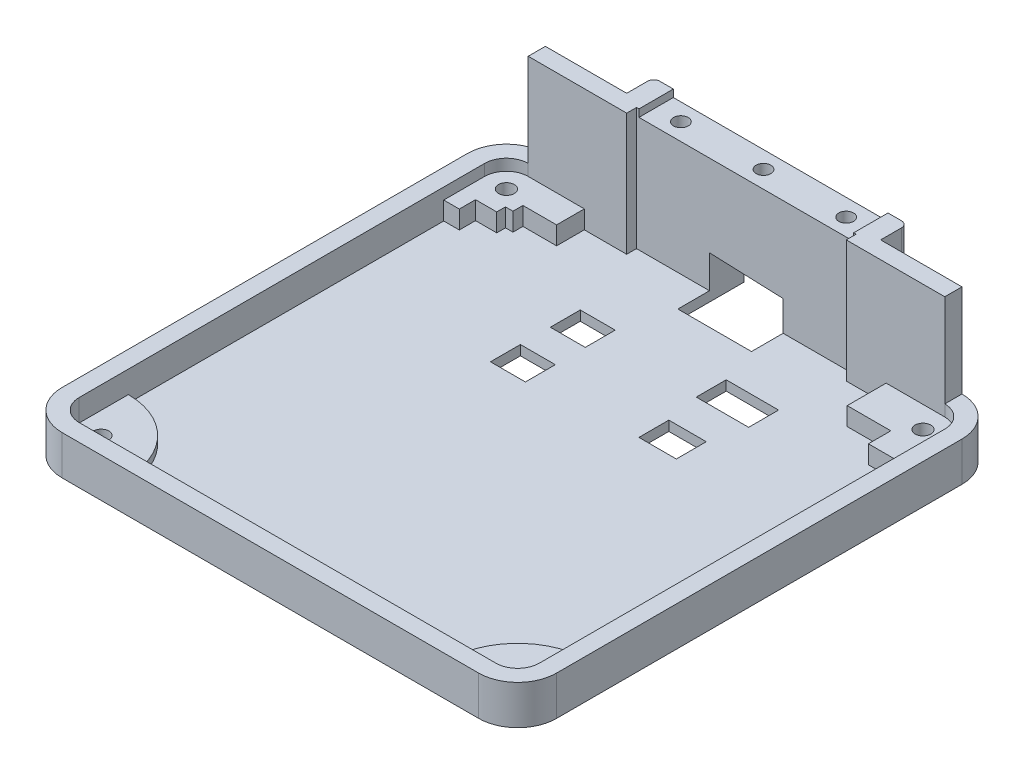
SolidWorks part; units mm, degrees
ref_plane "Front Plane" through (0, 0, 0) normal (0, 0, 1) x (1, 0, 0)
ref_plane "Top Plane" through (0, 0, 0) normal (0, 1, 0) x (1, 0, 0)
ref_plane "Right Plane" through (0, 0, 0) normal (1, 0, 0) x (0, 0, -1)
sketch "Sketch2" plane through (0, 0, 0) normal (0, 1, 0) x (1, 0, 0)
  line L6 (-46.8585, -41.275) -> (-46.8585, 41.275)
  line L8 (46.8585, -41.275) -> (46.8585, 41.275)
  line L9 (42.418, -45.7155) -> (-42.418, -45.7155)
  line L10 (-42.418, 45.7155) -> (-16.8754, 45.7155)
  line L11 (-46.8585, -41.275) -> (-50.3585, -41.275)
  line L14 (-50.3585, -41.275) -> (-50.3585, 41.275)
  line L15 (-42.418, 45.7155) -> (-42.418, 49.2155)
  line L16 (-42.418, 41.275) -> (-37.8452, 38.0373)
  line L17 (-42.418, 49.2155) -> (42.418, 49.2155)
  line L18 (-37.8452, 38.0373) -> (-37.8452, 40.0693)
  line L19 (-37.8452, 40.0693) -> (-30.9872, 40.0693)
  line L20 (-30.9872, 40.0693) -> (-30.9872, 45.7155)
  line L21 (-37.8452, 38.0373) -> (-39.3692, 38.0373)
  line L22 (46.8585, 41.275) -> (50.3585, 41.275)
  line L23 (42.418, -45.7155) -> (42.418, -49.2155)
  line L24 (-39.3692, 38.0373) -> (-39.3692, 36.2593)
  line L25 (42.418, -49.2155) -> (-42.418, -49.2155)
  line L26 (-39.3692, 36.2593) -> (-43.6872, 36.2593)
  line L27 (-43.6872, 36.2593) -> (-43.6872, 32.9573)
  line L28 (50.3585, 41.275) -> (50.3585, -41.275)
  line L34 (-43.6872, 32.9573) -> (-46.8585, 32.9573)
  line L37 (42.418, 41.275) -> (50.0148, 49.9834)
  line L46 (-16.2544, 31.1733) -> (-10.1584, 31.1733)
  line L52 (-10.1584, 31.1733) -> (-10.1584, 25.0773)
  line L58 (-10.1584, 25.0773) -> (-17.2704, 25.0773)
  line L64 (-17.2704, 25.0773) -> (-17.2704, 31.1733)
  line L70 (-17.2704, 31.1733) -> (-16.2544, 31.1733)
  line L76 (-17.2704, 25.0773) -> (-17.2704, 18.9813)
  line L82 (-17.2704, 18.9813) -> (-10.1584, 18.9813)
  line L88 (-10.1584, 18.9813) -> (-10.1584, 12.8853)
  line L94 (-10.1584, 12.8853) -> (-17.2704, 12.8853)
  line L100 (-17.2704, 12.8853) -> (-17.2704, 18.9813)
  line L111 (22.418, 45.7155) -> (42.418, 45.7155)
  line L112 (-10.1584, 31.1733) -> (9.9076, 31.1733)
  line L113 (9.9076, 31.1733) -> (9.9076, 33.7133)
  line L114 (9.9076, 33.7133) -> (20.5756, 33.7133)
  line L115 (20.5756, 33.7133) -> (20.5756, 27.6173)
  line L116 (20.5756, 27.6173) -> (9.9076, 27.6173)
  line L117 (9.9076, 27.6173) -> (9.9076, 31.1733)
  line L118 (9.9076, 27.6173) -> (9.9076, 20.7633)
  line L119 (9.9076, 20.7633) -> (18.7976, 20.7633)
  line L120 (18.7976, 20.7633) -> (18.7976, 14.6673)
  line L121 (18.7976, 14.6673) -> (11.1776, 14.6673)
  line L122 (11.1776, 14.6673) -> (11.1776, 20.7633)
  line L123 (42.418, 41.275) -> (0, 41.275)
  line L124 (42.418, 41.275) -> (39.3704, 37.7815)
  line L125 (39.3704, 37.7815) -> (39.3704, 33.2095)
  line L126 (39.3704, 37.7815) -> (30.4804, 37.7815)
  line L127 (30.4804, 37.7815) -> (30.4804, 45.7155)
  line L128 (39.3704, 33.2095) -> (46.8585, 33.2095)
  line L129 (22.418, 45.7155) -> (-16.8754, 45.7155)
  line L130 (46.8585, -41.275) -> (46.8585, -31.275)
  line L131 (42.418, -45.7155) -> (32.418, -45.7155)
  line L132 (-42.418, -45.7155) -> (-32.418, -45.7155)
  line L133 (-46.8585, -41.275) -> (-46.8585, -31.275)
  arc A0 (-42.418, 45.7155) -> (-46.8585, 41.275) centre (-42.418, 41.275) ccw
  arc A1 (42.418, 45.7155) -> (46.8585, 41.275) centre (42.418, 41.275) cw
  arc A2 (-46.8585, -41.275) -> (-42.418, -45.7155) centre (-42.418, -41.275) ccw
  arc A3 (46.8585, -41.275) -> (42.418, -45.7155) centre (42.418, -41.275) cw
  circle A4 centre (42.418, 41.275) radius 1.6
  circle A5 centre (-42.418, 41.275) radius 1.6
  circle A6 centre (-42.418, -41.275) radius 1.6
  circle A7 centre (42.418, -41.275) radius 1.6
  arc A8 (-42.418, 49.2155) -> (-50.3585, 41.275) centre (-42.418, 41.275) ccw
  arc A9 (42.418, 49.2155) -> (50.3585, 41.275) centre (42.418, 41.275) cw
  arc A10 (42.418, -49.2155) -> (50.3585, -41.275) centre (42.418, -41.275) ccw
  arc A11 (-42.418, -49.2155) -> (-50.3585, -41.275) centre (-42.418, -41.275) cw
  arc A12 (46.8585, -31.275) -> (32.418, -45.7155) centre (46.8585, -45.7155) ccw
  arc A13 (-46.8585, -31.275) -> (-32.418, -45.7155) centre (-46.8585, -45.7155) cw
extrude "Boss-Extrude1" add sketch "Sketch2" along normal blind 1.5 contours L8 A12 L9 A3 A7 | A13 L6 A2 L9 A6 region at (-40.4967, 0, 39.3537) region at (40.4967, 0, 39.3537)
sketch "Sketch5" plane through (0, 0, 0) normal (0, -1, 0) x (1, 0, 0)
  line L0 (-17.2704, -25.0773) -> (-17.2704, -18.9813) construction
  line L1 (42.418, -41.275) -> (50.0148, -49.9834) construction
  line L2 (42.418, -41.275) -> (0, -41.275) construction
  line L3 (42.418, -41.275) -> (39.3704, -37.7815) construction
  line L4 (-42.418, -41.275) -> (-37.8452, -38.0373) construction
  line L5 (-42.418, -45.7155) -> (-16.8754, -45.7155) construction
  line L6 (22.418, -45.7155) -> (-16.8754, -45.7155) construction
  line L7 (22.418, -45.7155) -> (42.418, -45.7155) construction
  line L8 (-42.418, -45.7155) -> (-42.418, -49.2155) construction
  line L9 (-46.8585, 41.275) -> (-46.8585, -41.275) construction
  line L10 (42.418, 45.7155) -> (-42.418, 45.7155) construction
  line L11 (-42.418, 45.7155) -> (-32.418, 45.7155) construction
  line L12 (-46.8585, 41.275) -> (-46.8585, 31.275) construction
  line L13 (42.418, 45.7155) -> (42.418, 49.2155) construction
  line L14 (46.8585, 41.275) -> (46.8585, 31.275) construction
  line L15 (42.418, 45.7155) -> (32.418, 45.7155) construction
  line L16 (46.8585, 41.275) -> (46.8585, -41.275) construction
  line L17 (46.8585, -41.275) -> (50.3585, -41.275) construction
  line L18 (-46.8585, 41.275) -> (-50.3585, 41.275) construction
  line L19 (-37.8452, -38.0373) -> (-39.3692, -38.0373) construction
  line L20 (-39.3692, -38.0373) -> (-39.3692, -36.2593) construction
  line L21 (-39.3692, -36.2593) -> (-43.6872, -36.2593) construction
  line L22 (-43.6872, -36.2593) -> (-43.6872, -32.9573) construction
  line L23 (-43.6872, -32.9573) -> (-46.8585, -32.9573) construction
  line L24 (-37.8452, -38.0373) -> (-37.8452, -40.0693) construction
  line L25 (-37.8452, -40.0693) -> (-30.9872, -40.0693) construction
  line L26 (-30.9872, -40.0693) -> (-30.9872, -45.7155) construction
  line L27 (-42.418, -49.2155) -> (42.418, -49.2155) construction
  line L28 (-50.3585, 41.275) -> (-50.3585, -41.275) construction
  line L29 (42.418, 49.2155) -> (-42.418, 49.2155) construction
  line L30 (9.9076, -31.1733) -> (9.9076, -33.7133) construction
  line L31 (9.9076, -33.7133) -> (20.5756, -33.7133) construction
  line L32 (20.5756, -33.7133) -> (20.5756, -27.6173) construction
  line L33 (20.5756, -27.6173) -> (9.9076, -27.6173) construction
  line L34 (9.9076, -27.6173) -> (9.9076, -31.1733) construction
  line L35 (9.9076, -27.6173) -> (9.9076, -20.7633) construction
  line L36 (9.9076, -20.7633) -> (18.7976, -20.7633) construction
  line L37 (18.7976, -20.7633) -> (18.7976, -14.6673) construction
  line L38 (18.7976, -14.6673) -> (11.1776, -14.6673) construction
  line L39 (11.1776, -14.6673) -> (11.1776, -20.7633) construction
  line L40 (-10.1584, -31.1733) -> (9.9076, -31.1733) construction
  line L41 (50.3585, -41.275) -> (50.3585, 41.275) construction
  line L42 (39.3704, -37.7815) -> (39.3704, -33.2095) construction
  line L43 (39.3704, -33.2095) -> (46.8585, -33.2095) construction
  line L44 (39.3704, -37.7815) -> (30.4804, -37.7815) construction
  line L45 (30.4804, -37.7815) -> (30.4804, -45.7155) construction
  line L46 (-10.1584, -31.1733) -> (-10.1584, -25.0773) construction
  line L47 (-10.1584, -25.0773) -> (-17.2704, -25.0773) construction
  line L48 (-16.2544, -31.1733) -> (-10.1584, -31.1733) construction
  line L49 (-17.2704, -31.1733) -> (-16.2544, -31.1733) construction
  line L50 (-17.2704, -25.0773) -> (-17.2704, -31.1733) construction
  line L51 (-17.2704, -18.9813) -> (-10.1584, -18.9813) construction
  line L52 (-10.1584, -18.9813) -> (-10.1584, -12.8853) construction
  line L53 (-10.1584, -12.8853) -> (-17.2704, -12.8853) construction
  line L54 (-17.2704, -12.8853) -> (-17.2704, -18.9813) construction
  line L55 (-17.2704, -25.0773) -> (-17.2704, -18.9813)
  line L56 (42.418, -41.275) -> (50.0148, -49.9834)
  line L57 (42.418, -41.275) -> (0, -41.275)
  line L58 (42.418, -41.275) -> (39.3704, -37.7815)
  line L59 (-42.418, -41.275) -> (-37.8452, -38.0373)
  line L60 (-42.418, -45.7155) -> (-16.8754, -45.7155)
  line L61 (22.418, -45.7155) -> (-16.8754, -45.7155)
  line L62 (22.418, -45.7155) -> (42.418, -45.7155)
  line L63 (-42.418, -45.7155) -> (-42.418, -49.2155)
  line L64 (-46.8585, 41.275) -> (-46.8585, -41.275)
  line L65 (42.418, 45.7155) -> (-42.418, 45.7155)
  line L66 (-42.418, 45.7155) -> (-32.418, 45.7155)
  line L67 (-46.8585, 41.275) -> (-46.8585, 31.275)
  line L68 (42.418, 45.7155) -> (42.418, 49.2155)
  line L69 (46.8585, 41.275) -> (46.8585, 31.275)
  line L70 (42.418, 45.7155) -> (32.418, 45.7155)
  line L71 (46.8585, 41.275) -> (46.8585, -41.275)
  line L72 (46.8585, -41.275) -> (50.3585, -41.275)
  line L73 (-46.8585, 41.275) -> (-50.3585, 41.275)
  line L74 (-37.8452, -38.0373) -> (-39.3692, -38.0373)
  line L75 (-39.3692, -38.0373) -> (-39.3692, -36.2593)
  line L76 (-39.3692, -36.2593) -> (-43.6872, -36.2593)
  line L77 (-43.6872, -36.2593) -> (-43.6872, -32.9573)
  line L78 (-43.6872, -32.9573) -> (-46.8585, -32.9573)
  line L79 (-37.8452, -38.0373) -> (-37.8452, -40.0693)
  line L80 (-37.8452, -40.0693) -> (-30.9872, -40.0693)
  line L81 (-30.9872, -40.0693) -> (-30.9872, -45.7155)
  line L82 (-42.418, -49.2155) -> (42.418, -49.2155)
  line L83 (-50.3585, 41.275) -> (-50.3585, -41.275)
  line L84 (42.418, 49.2155) -> (-42.418, 49.2155)
  line L85 (9.9076, -31.1733) -> (9.9076, -33.7133)
  line L86 (9.9076, -33.7133) -> (20.5756, -33.7133)
  line L87 (20.5756, -33.7133) -> (20.5756, -27.6173)
  line L88 (20.5756, -27.6173) -> (9.9076, -27.6173)
  line L89 (9.9076, -27.6173) -> (9.9076, -31.1733)
  line L90 (9.9076, -27.6173) -> (9.9076, -20.7633)
  line L91 (9.9076, -20.7633) -> (18.7976, -20.7633)
  line L92 (18.7976, -20.7633) -> (18.7976, -14.6673)
  line L93 (18.7976, -14.6673) -> (11.1776, -14.6673)
  line L94 (11.1776, -14.6673) -> (11.1776, -20.7633)
  line L95 (-10.1584, -31.1733) -> (9.9076, -31.1733)
  line L96 (50.3585, -41.275) -> (50.3585, 41.275)
  line L97 (39.3704, -37.7815) -> (39.3704, -33.2095)
  line L98 (39.3704, -33.2095) -> (46.8585, -33.2095)
  line L99 (39.3704, -37.7815) -> (30.4804, -37.7815)
  line L100 (30.4804, -37.7815) -> (30.4804, -45.7155)
  line L101 (-10.1584, -31.1733) -> (-10.1584, -25.0773)
  line L102 (-10.1584, -25.0773) -> (-17.2704, -25.0773)
  line L103 (-16.2544, -31.1733) -> (-10.1584, -31.1733)
  line L104 (-17.2704, -31.1733) -> (-16.2544, -31.1733)
  line L105 (-17.2704, -25.0773) -> (-17.2704, -31.1733)
  line L106 (-17.2704, -18.9813) -> (-10.1584, -18.9813)
  line L107 (-10.1584, -18.9813) -> (-10.1584, -12.8853)
  line L108 (-10.1584, -12.8853) -> (-17.2704, -12.8853)
  line L109 (-17.2704, -12.8853) -> (-17.2704, -18.9813)
  line L110 (50.3585, -41.275) -> (50.3585, 41.275)
  line L111 (42.418, 49.2155) -> (-42.418, 49.2155)
  line L112 (-50.3585, 41.275) -> (-50.3585, -41.275)
  line L113 (-42.418, -49.2155) -> (42.418, -49.2155)
  arc A0 (42.418, -45.7155) -> (46.8585, -41.275) centre (42.418, -41.275) ccw construction
  arc A1 (-46.8585, -41.275) -> (-42.418, -45.7155) centre (-42.418, -41.275) ccw construction
  arc A2 (-46.8585, 31.275) -> (-32.418, 45.7155) centre (-46.8585, 45.7155) ccw construction
  arc A3 (-42.418, 45.7155) -> (-46.8585, 41.275) centre (-42.418, 41.275) ccw construction
  arc A4 (32.418, 45.7155) -> (46.8585, 31.275) centre (46.8585, 45.7155) ccw construction
  arc A5 (46.8585, 41.275) -> (42.418, 45.7155) centre (42.418, 41.275) ccw construction
  arc A6 (42.418, -49.2155) -> (50.3585, -41.275) centre (42.418, -41.275) ccw construction
  arc A7 (-50.3585, -41.275) -> (-42.418, -49.2155) centre (-42.418, -41.275) ccw construction
  arc A8 (-42.418, 49.2155) -> (-50.3585, 41.275) centre (-42.418, 41.275) ccw construction
  arc A9 (50.3585, 41.275) -> (42.418, 49.2155) centre (42.418, 41.275) ccw construction
  circle A10 centre (42.418, 41.275) radius 1.6 construction
  circle A11 centre (-42.418, 41.275) radius 1.6 construction
  circle A12 centre (-42.418, -41.275) radius 1.6 construction
  circle A13 centre (42.418, -41.275) radius 1.6 construction
  arc A14 (42.418, -45.7155) -> (46.8585, -41.275) centre (42.418, -41.275) ccw
  arc A15 (-46.8585, -41.275) -> (-42.418, -45.7155) centre (-42.418, -41.275) ccw
  arc A16 (-46.8585, 31.275) -> (-32.418, 45.7155) centre (-46.8585, 45.7155) ccw
  arc A17 (-42.418, 45.7155) -> (-46.8585, 41.275) centre (-42.418, 41.275) ccw
  arc A18 (32.418, 45.7155) -> (46.8585, 31.275) centre (46.8585, 45.7155) ccw
  arc A19 (46.8585, 41.275) -> (42.418, 45.7155) centre (42.418, 41.275) ccw
  arc A20 (42.418, -49.2155) -> (50.3585, -41.275) centre (42.418, -41.275) ccw
  arc A21 (-50.3585, -41.275) -> (-42.418, -49.2155) centre (-42.418, -41.275) ccw
  arc A22 (-42.418, 49.2155) -> (-50.3585, 41.275) centre (-42.418, 41.275) ccw
  arc A23 (50.3585, 41.275) -> (42.418, 49.2155) centre (42.418, 41.275) ccw
  circle A24 centre (42.418, 41.275) radius 1.6
  circle A25 centre (-42.418, 41.275) radius 1.6
  circle A26 centre (-42.418, -41.275) radius 1.6
  circle A27 centre (42.418, -41.275) radius 1.6
  arc A28 (42.418, -49.2155) -> (50.3585, -41.275) centre (42.418, -41.275) ccw
  arc A29 (50.3585, 41.275) -> (42.418, 49.2155) centre (42.418, 41.275) ccw
  arc A30 (-42.418, 49.2155) -> (-50.3585, 41.275) centre (-42.418, 41.275) ccw
  arc A31 (-50.3585, -41.275) -> (-42.418, -49.2155) centre (-42.418, -41.275) ccw
  arc M1 (-46.8585, 31.275) -> (-32.418, 45.7155) centre (-46.8585, 45.7155) ccw
  line M2 (-32.418, 45.7155) -> (-42.418, 45.7155)
  arc M3 (-42.418, 45.7155) -> (-46.8585, 41.275) centre (-42.418, 41.275) ccw
  line M4 (-46.8585, 41.275) -> (-46.8585, 31.275)
  circle M5 centre (-42.418, 41.275) radius 1.6
extrude "Boss-Extrude3" add sketch "Sketch5" along normal blind 2 contours L82 A20 L56 A14 L62 L61 L60 L63 | L56 A20 L72 A14 | L96 A23 L68 A19 L69 L71 L72 | A18 L65 L64 L78 L77 L76 L75 L74 L79 L80 L81 L60 L61 L62 L100 L99 L97 L98 L71 L109 L108 L107 L106 L102 L101 L89 L94 L93 L92 L91 L88 L87 L86 L85 L103 L104 L105 M1 | A27 L58 L99 L100 L57 | A27 L57 L100 L62 A14 L56 | A27 L56 A14 L71 L98 L97 L58 | A26 L74 L75 L76 L77 L78 L64 A15 L60 L81 L80 L79 | M4 M1 M2 M3 M5 | L69 A19 L65 A18 A24 | L84 A22 L73 L65 L68 M3 M2 | L83 A21 L63 A15 L64 L73 M4 region at (43.6425, 0, -37.4818) region at (37.0258, 0, -43.6304) region at (35.5464, 0, -39.5753) region at (48.0295, 0, -43.8264) region at (2.2185, 0, -47.4473) region at (-0.2178, 0, 0.4927) region at (48.3825, 0, 4.776) region at (-48.3825, 0, -4.776) region at (40.4967, 0, 39.3537) region at (-39.9913, 0, -40.9811) region at (-4.7781, 0, 47.245) region at (-40.4967, 0, 39.3537)
sketch "Sketch6" plane through (0, 0, 0) normal (0, 1, 0) x (1, 0, 0)
  line L0 (-17.2704, 25.0773) -> (-17.2704, 18.9813) construction
  line L1 (42.418, 41.275) -> (50.0148, 49.9834) construction
  line L2 (42.418, 41.275) -> (0, 41.275) construction
  line L3 (42.418, 41.275) -> (39.3704, 37.7815) construction
  line L4 (-42.418, 41.275) -> (-37.8452, 38.0373) construction
  line L5 (-42.418, 45.7155) -> (-16.8754, 45.7155) construction
  line L6 (22.418, 45.7155) -> (-16.8754, 45.7155) construction
  line L7 (22.418, 45.7155) -> (42.418, 45.7155) construction
  line L8 (-42.418, 45.7155) -> (-42.418, 49.2155) construction
  line L9 (-46.8585, -41.275) -> (-46.8585, 41.275) construction
  line L10 (42.418, -45.7155) -> (-42.418, -45.7155) construction
  line L11 (-42.418, -45.7155) -> (-32.418, -45.7155) construction
  line L12 (-46.8585, -41.275) -> (-46.8585, -31.275) construction
  line L13 (42.418, -45.7155) -> (42.418, -49.2155) construction
  line L14 (46.8585, -41.275) -> (46.8585, -31.275) construction
  line L15 (42.418, -45.7155) -> (32.418, -45.7155) construction
  line L16 (46.8585, -41.275) -> (46.8585, 41.275) construction
  line L17 (46.8585, 41.275) -> (50.3585, 41.275) construction
  line L18 (-46.8585, -41.275) -> (-50.3585, -41.275) construction
  line L19 (-37.8452, 38.0373) -> (-39.3692, 38.0373) construction
  line L20 (-39.3692, 38.0373) -> (-39.3692, 36.2593) construction
  line L21 (-39.3692, 36.2593) -> (-43.6872, 36.2593) construction
  line L22 (-43.6872, 36.2593) -> (-43.6872, 32.9573) construction
  line L23 (-43.6872, 32.9573) -> (-46.8585, 32.9573) construction
  line L24 (-37.8452, 38.0373) -> (-37.8452, 40.0693) construction
  line L25 (-37.8452, 40.0693) -> (-30.9872, 40.0693) construction
  line L26 (-30.9872, 40.0693) -> (-30.9872, 45.7155) construction
  line L27 (-42.418, 49.2155) -> (42.418, 49.2155) construction
  line L28 (-50.3585, -41.275) -> (-50.3585, 41.275) construction
  line L29 (42.418, -49.2155) -> (-42.418, -49.2155) construction
  line L30 (9.9076, 31.1733) -> (9.9076, 33.7133) construction
  line L31 (9.9076, 33.7133) -> (20.5756, 33.7133) construction
  line L32 (20.5756, 33.7133) -> (20.5756, 27.6173) construction
  line L33 (20.5756, 27.6173) -> (9.9076, 27.6173) construction
  line L34 (9.9076, 27.6173) -> (9.9076, 31.1733) construction
  line L35 (9.9076, 27.6173) -> (9.9076, 20.7633) construction
  line L36 (9.9076, 20.7633) -> (18.7976, 20.7633) construction
  line L37 (18.7976, 20.7633) -> (18.7976, 14.6673) construction
  line L38 (18.7976, 14.6673) -> (11.1776, 14.6673) construction
  line L39 (11.1776, 14.6673) -> (11.1776, 20.7633) construction
  line L40 (-10.1584, 31.1733) -> (9.9076, 31.1733) construction
  line L41 (50.3585, 41.275) -> (50.3585, -41.275) construction
  line L42 (39.3704, 37.7815) -> (39.3704, 33.2095) construction
  line L43 (39.3704, 33.2095) -> (46.8585, 33.2095) construction
  line L44 (39.3704, 37.7815) -> (30.4804, 37.7815) construction
  line L45 (30.4804, 37.7815) -> (30.4804, 45.7155) construction
  line L46 (-10.1584, 31.1733) -> (-10.1584, 25.0773) construction
  line L47 (-10.1584, 25.0773) -> (-17.2704, 25.0773) construction
  line L48 (-16.2544, 31.1733) -> (-10.1584, 31.1733) construction
  line L49 (-17.2704, 31.1733) -> (-16.2544, 31.1733) construction
  line L50 (-17.2704, 25.0773) -> (-17.2704, 31.1733) construction
  line L51 (-17.2704, 18.9813) -> (-10.1584, 18.9813) construction
  line L52 (-10.1584, 18.9813) -> (-10.1584, 12.8853) construction
  line L53 (-10.1584, 12.8853) -> (-17.2704, 12.8853) construction
  line L54 (-17.2704, 12.8853) -> (-17.2704, 18.9813) construction
  line L55 (-17.2704, 25.0773) -> (-17.2704, 18.9813)
  line L56 (42.418, 41.275) -> (50.0148, 49.9834)
  line L57 (42.418, 41.275) -> (0, 41.275)
  line L58 (42.418, 41.275) -> (39.3704, 37.7815)
  line L59 (-42.418, 41.275) -> (-37.8452, 38.0373)
  line L60 (-42.418, 45.7155) -> (-16.8754, 45.7155)
  line L61 (22.418, 45.7155) -> (-16.8754, 45.7155)
  line L62 (22.418, 45.7155) -> (42.418, 45.7155)
  line L63 (-42.418, 45.7155) -> (-42.418, 49.2155)
  line L64 (-46.8585, -41.275) -> (-46.8585, 41.275)
  line L65 (42.418, -45.7155) -> (-42.418, -45.7155)
  line L66 (-42.418, -45.7155) -> (-32.418, -45.7155)
  line L67 (-46.8585, -41.275) -> (-46.8585, -31.275)
  line L68 (42.418, -45.7155) -> (42.418, -49.2155)
  line L69 (46.8585, -41.275) -> (46.8585, -31.275)
  line L70 (42.418, -45.7155) -> (32.418, -45.7155)
  line L71 (46.8585, -41.275) -> (46.8585, 41.275)
  line L72 (46.8585, 41.275) -> (50.3585, 41.275)
  line L73 (-46.8585, -41.275) -> (-50.3585, -41.275)
  line L74 (-37.8452, 38.0373) -> (-39.3692, 38.0373)
  line L75 (-39.3692, 38.0373) -> (-39.3692, 36.2593)
  line L76 (-39.3692, 36.2593) -> (-43.6872, 36.2593)
  line L77 (-43.6872, 36.2593) -> (-43.6872, 32.9573)
  line L78 (-43.6872, 32.9573) -> (-46.8585, 32.9573)
  line L79 (-37.8452, 38.0373) -> (-37.8452, 40.0693)
  line L80 (-37.8452, 40.0693) -> (-30.9872, 40.0693)
  line L81 (-30.9872, 40.0693) -> (-30.9872, 45.7155)
  line L82 (-42.418, 49.2155) -> (42.418, 49.2155)
  line L83 (-50.3585, -41.275) -> (-50.3585, 41.275)
  line L84 (42.418, -49.2155) -> (-42.418, -49.2155)
  line L85 (9.9076, 31.1733) -> (9.9076, 33.7133)
  line L86 (9.9076, 33.7133) -> (20.5756, 33.7133)
  line L87 (20.5756, 33.7133) -> (20.5756, 27.6173)
  line L88 (20.5756, 27.6173) -> (9.9076, 27.6173)
  line L89 (9.9076, 27.6173) -> (9.9076, 31.1733)
  line L90 (9.9076, 27.6173) -> (9.9076, 20.7633)
  line L91 (9.9076, 20.7633) -> (18.7976, 20.7633)
  line L92 (18.7976, 20.7633) -> (18.7976, 14.6673)
  line L93 (18.7976, 14.6673) -> (11.1776, 14.6673)
  line L94 (11.1776, 14.6673) -> (11.1776, 20.7633)
  line L95 (-10.1584, 31.1733) -> (9.9076, 31.1733)
  line L96 (50.3585, 41.275) -> (50.3585, -41.275)
  line L97 (39.3704, 37.7815) -> (39.3704, 33.2095)
  line L98 (39.3704, 33.2095) -> (46.8585, 33.2095)
  line L99 (39.3704, 37.7815) -> (30.4804, 37.7815)
  line L100 (30.4804, 37.7815) -> (30.4804, 45.7155)
  line L101 (-10.1584, 31.1733) -> (-10.1584, 25.0773)
  line L102 (-10.1584, 25.0773) -> (-17.2704, 25.0773)
  line L103 (-16.2544, 31.1733) -> (-10.1584, 31.1733)
  line L104 (-17.2704, 31.1733) -> (-16.2544, 31.1733)
  line L105 (-17.2704, 25.0773) -> (-17.2704, 31.1733)
  line L106 (-17.2704, 18.9813) -> (-10.1584, 18.9813)
  line L107 (-10.1584, 18.9813) -> (-10.1584, 12.8853)
  line L108 (-10.1584, 12.8853) -> (-17.2704, 12.8853)
  line L109 (-17.2704, 12.8853) -> (-17.2704, 18.9813)
  line L110 (30.4804, 45.7155) -> (30.4804, 37.7815)
  line L111 (39.3704, 37.7815) -> (39.3704, 33.2095)
  line L112 (30.4804, 37.7815) -> (39.3704, 37.7815)
  line L113 (39.3704, 33.2095) -> (46.8585, 33.2095)
  line L114 (46.8585, 33.2095) -> (46.8585, 41.275)
  line L115 (42.418, 45.7155) -> (30.4804, 45.7155)
  line L116 (-42.418, 45.7155) -> (-30.9872, 45.7155)
  line L117 (-30.9872, 45.7155) -> (-30.9872, 40.0693)
  line L118 (-30.9872, 40.0693) -> (-37.8452, 40.0693)
  line L119 (-37.8452, 40.0693) -> (-37.8452, 38.0373)
  line L120 (-37.8452, 38.0373) -> (-39.3692, 38.0373)
  line L121 (-39.3692, 38.0373) -> (-39.3692, 36.2593)
  line L122 (-39.3692, 36.2593) -> (-43.6872, 36.2593)
  line L123 (-43.6872, 36.2593) -> (-43.6872, 32.9573)
  line L124 (-43.6872, 32.9573) -> (-46.8585, 32.9573)
  line L125 (-46.8585, 32.9573) -> (-46.8585, 41.275)
  arc A0 (46.8585, 41.275) -> (42.418, 45.7155) centre (42.418, 41.275) ccw construction
  arc A1 (-42.418, 45.7155) -> (-46.8585, 41.275) centre (-42.418, 41.275) ccw construction
  arc A2 (-32.418, -45.7155) -> (-46.8585, -31.275) centre (-46.8585, -45.7155) ccw construction
  arc A3 (-46.8585, -41.275) -> (-42.418, -45.7155) centre (-42.418, -41.275) ccw construction
  arc A4 (46.8585, -31.275) -> (32.418, -45.7155) centre (46.8585, -45.7155) ccw construction
  arc A5 (42.418, -45.7155) -> (46.8585, -41.275) centre (42.418, -41.275) ccw construction
  arc A6 (50.3585, 41.275) -> (42.418, 49.2155) centre (42.418, 41.275) ccw construction
  arc A7 (-42.418, 49.2155) -> (-50.3585, 41.275) centre (-42.418, 41.275) ccw construction
  arc A8 (-50.3585, -41.275) -> (-42.418, -49.2155) centre (-42.418, -41.275) ccw construction
  arc A9 (42.418, -49.2155) -> (50.3585, -41.275) centre (42.418, -41.275) ccw construction
  circle A10 centre (42.418, -41.275) radius 1.6 construction
  circle A11 centre (-42.418, -41.275) radius 1.6 construction
  circle A12 centre (-42.418, 41.275) radius 1.6 construction
  circle A13 centre (42.418, 41.275) radius 1.6 construction
  arc A14 (46.8585, 41.275) -> (42.418, 45.7155) centre (42.418, 41.275) ccw
  arc A15 (-42.418, 45.7155) -> (-46.8585, 41.275) centre (-42.418, 41.275) ccw
  arc A16 (-32.418, -45.7155) -> (-46.8585, -31.275) centre (-46.8585, -45.7155) ccw
  arc A17 (-46.8585, -41.275) -> (-42.418, -45.7155) centre (-42.418, -41.275) ccw
  arc A18 (46.8585, -31.275) -> (32.418, -45.7155) centre (46.8585, -45.7155) ccw
  arc A19 (42.418, -45.7155) -> (46.8585, -41.275) centre (42.418, -41.275) ccw
  arc A20 (50.3585, 41.275) -> (42.418, 49.2155) centre (42.418, 41.275) ccw
  arc A21 (-42.418, 49.2155) -> (-50.3585, 41.275) centre (-42.418, 41.275) ccw
  arc A22 (-50.3585, -41.275) -> (-42.418, -49.2155) centre (-42.418, -41.275) ccw
  arc A23 (42.418, -49.2155) -> (50.3585, -41.275) centre (42.418, -41.275) ccw
  circle A24 centre (42.418, -41.275) radius 1.6
  circle A25 centre (-42.418, -41.275) radius 1.6
  circle A26 centre (-42.418, 41.275) radius 1.6
  circle A27 centre (42.418, 41.275) radius 1.6
  arc A28 (-46.8585, 41.275) -> (-42.418, 45.7155) centre (-42.418, 41.275) cw
  arc A29 (46.8585, 41.275) -> (42.418, 45.7155) centre (42.418, 41.275) ccw
  circle M17 centre (42.418, 41.275) radius 1.6
  circle M34 centre (-42.418, 41.275) radius 1.6
extrude "Boss-Extrude4" add sketch "Sketch6" along normal blind 3.7 contours L56 A14 L62 L100 L57 M17 | L100 L99 L58 L57 M17 | L71 A14 L56 L58 L97 L98 M17 | L60 A15 L64 L78 L77 L76 L75 L74 L79 L80 L81 M34 region at (37.0258, 0, -43.6304) region at (43.6425, 0, -37.4818) region at (35.5464, 0, -39.5753) region at (-39.9913, 0, -40.9811)
sketch "Sketch7" plane through (0, 0, 0) normal (0, 1, 0) x (1, 0, 0)
  line L0 (-17.2704, 25.0773) -> (-17.2704, 18.9813) construction
  line L1 (42.418, 41.275) -> (50.0148, 49.9834) construction
  line L2 (42.418, 41.275) -> (0, 41.275) construction
  line L3 (42.418, 41.275) -> (39.3704, 37.7815) construction
  line L4 (-42.418, 41.275) -> (-37.8452, 38.0373) construction
  line L5 (-42.418, 45.7155) -> (-16.8754, 45.7155) construction
  line L6 (22.418, 45.7155) -> (-16.8754, 45.7155) construction
  line L7 (22.418, 45.7155) -> (42.418, 45.7155) construction
  line L8 (-42.418, 45.7155) -> (-42.418, 49.2155) construction
  line L9 (-46.8585, -41.275) -> (-46.8585, 41.275) construction
  line L10 (42.418, -45.7155) -> (-42.418, -45.7155) construction
  line L11 (-42.418, -45.7155) -> (-32.418, -45.7155) construction
  line L12 (-46.8585, -41.275) -> (-46.8585, -31.275) construction
  line L13 (42.418, -45.7155) -> (42.418, -49.2155) construction
  line L14 (46.8585, -41.275) -> (46.8585, -31.275) construction
  line L15 (42.418, -45.7155) -> (32.418, -45.7155) construction
  line L16 (46.8585, -41.275) -> (46.8585, 41.275) construction
  line L17 (46.8585, 41.275) -> (50.3585, 41.275) construction
  line L18 (-46.8585, -41.275) -> (-50.3585, -41.275) construction
  line L19 (-37.8452, 38.0373) -> (-39.3692, 38.0373) construction
  line L20 (-39.3692, 38.0373) -> (-39.3692, 36.2593) construction
  line L21 (-39.3692, 36.2593) -> (-43.6872, 36.2593) construction
  line L22 (-43.6872, 36.2593) -> (-43.6872, 32.9573) construction
  line L23 (-43.6872, 32.9573) -> (-46.8585, 32.9573) construction
  line L24 (-37.8452, 38.0373) -> (-37.8452, 40.0693) construction
  line L25 (-37.8452, 40.0693) -> (-30.9872, 40.0693) construction
  line L26 (-30.9872, 40.0693) -> (-30.9872, 45.7155) construction
  line L27 (-42.418, 49.2155) -> (42.418, 49.2155) construction
  line L28 (-50.3585, -41.275) -> (-50.3585, 41.275) construction
  line L29 (42.418, -49.2155) -> (-42.418, -49.2155) construction
  line L30 (9.9076, 31.1733) -> (9.9076, 33.7133) construction
  line L31 (9.9076, 33.7133) -> (20.5756, 33.7133) construction
  line L32 (20.5756, 33.7133) -> (20.5756, 27.6173) construction
  line L33 (20.5756, 27.6173) -> (9.9076, 27.6173) construction
  line L34 (9.9076, 27.6173) -> (9.9076, 31.1733) construction
  line L35 (9.9076, 27.6173) -> (9.9076, 20.7633) construction
  line L36 (9.9076, 20.7633) -> (18.7976, 20.7633) construction
  line L37 (18.7976, 20.7633) -> (18.7976, 14.6673) construction
  line L38 (18.7976, 14.6673) -> (11.1776, 14.6673) construction
  line L39 (11.1776, 14.6673) -> (11.1776, 20.7633) construction
  line L40 (-10.1584, 31.1733) -> (9.9076, 31.1733) construction
  line L41 (50.3585, 41.275) -> (50.3585, -41.275) construction
  line L42 (39.3704, 37.7815) -> (39.3704, 33.2095) construction
  line L43 (39.3704, 33.2095) -> (46.8585, 33.2095) construction
  line L44 (39.3704, 37.7815) -> (30.4804, 37.7815) construction
  line L45 (30.4804, 37.7815) -> (30.4804, 45.7155) construction
  line L46 (-10.1584, 31.1733) -> (-10.1584, 25.0773) construction
  line L47 (-10.1584, 25.0773) -> (-17.2704, 25.0773) construction
  line L48 (-16.2544, 31.1733) -> (-10.1584, 31.1733) construction
  line L49 (-17.2704, 31.1733) -> (-16.2544, 31.1733) construction
  line L50 (-17.2704, 25.0773) -> (-17.2704, 31.1733) construction
  line L51 (-17.2704, 18.9813) -> (-10.1584, 18.9813) construction
  line L52 (-10.1584, 18.9813) -> (-10.1584, 12.8853) construction
  line L53 (-10.1584, 12.8853) -> (-17.2704, 12.8853) construction
  line L54 (-17.2704, 12.8853) -> (-17.2704, 18.9813) construction
  line L55 (-17.2704, 25.0773) -> (-17.2704, 18.9813)
  line L56 (42.418, 41.275) -> (50.0148, 49.9834)
  line L57 (42.418, 41.275) -> (0, 41.275)
  line L58 (42.418, 41.275) -> (39.3704, 37.7815)
  line L59 (-42.418, 41.275) -> (-37.8452, 38.0373)
  line L60 (-42.418, 45.7155) -> (-16.8754, 45.7155)
  line L61 (22.418, 45.7155) -> (-16.8754, 45.7155)
  line L62 (22.418, 45.7155) -> (42.418, 45.7155)
  line L63 (-42.418, 45.7155) -> (-42.418, 49.2155)
  line L64 (-46.8585, -41.275) -> (-46.8585, 41.275)
  line L65 (42.418, -45.7155) -> (-42.418, -45.7155)
  line L66 (-42.418, -45.7155) -> (-32.418, -45.7155)
  line L67 (-46.8585, -41.275) -> (-46.8585, -31.275)
  line L68 (42.418, -45.7155) -> (42.418, -49.2155)
  line L69 (46.8585, -41.275) -> (46.8585, -31.275)
  line L70 (42.418, -45.7155) -> (32.418, -45.7155)
  line L71 (46.8585, -41.275) -> (46.8585, 41.275)
  line L72 (46.8585, 41.275) -> (50.3585, 41.275)
  line L73 (-46.8585, -41.275) -> (-50.3585, -41.275)
  line L74 (-37.8452, 38.0373) -> (-39.3692, 38.0373)
  line L75 (-39.3692, 38.0373) -> (-39.3692, 36.2593)
  line L76 (-39.3692, 36.2593) -> (-43.6872, 36.2593)
  line L77 (-43.6872, 36.2593) -> (-43.6872, 32.9573)
  line L78 (-43.6872, 32.9573) -> (-46.8585, 32.9573)
  line L79 (-37.8452, 38.0373) -> (-37.8452, 40.0693)
  line L80 (-37.8452, 40.0693) -> (-30.9872, 40.0693)
  line L81 (-30.9872, 40.0693) -> (-30.9872, 45.7155)
  line L82 (-42.418, 49.2155) -> (42.418, 49.2155)
  line L83 (-50.3585, -41.275) -> (-50.3585, 41.275)
  line L84 (42.418, -49.2155) -> (-42.418, -49.2155)
  line L85 (9.9076, 31.1733) -> (9.9076, 33.7133)
  line L86 (9.9076, 33.7133) -> (20.5756, 33.7133)
  line L87 (20.5756, 33.7133) -> (20.5756, 27.6173)
  line L88 (20.5756, 27.6173) -> (9.9076, 27.6173)
  line L89 (9.9076, 27.6173) -> (9.9076, 31.1733)
  line L90 (9.9076, 27.6173) -> (9.9076, 20.7633)
  line L91 (9.9076, 20.7633) -> (18.7976, 20.7633)
  line L92 (18.7976, 20.7633) -> (18.7976, 14.6673)
  line L93 (18.7976, 14.6673) -> (11.1776, 14.6673)
  line L94 (11.1776, 14.6673) -> (11.1776, 20.7633)
  line L95 (-10.1584, 31.1733) -> (9.9076, 31.1733)
  line L96 (50.3585, 41.275) -> (50.3585, -41.275)
  line L97 (39.3704, 37.7815) -> (39.3704, 33.2095)
  line L98 (39.3704, 33.2095) -> (46.8585, 33.2095)
  line L99 (39.3704, 37.7815) -> (30.4804, 37.7815)
  line L100 (30.4804, 37.7815) -> (30.4804, 45.7155)
  line L101 (-10.1584, 31.1733) -> (-10.1584, 25.0773)
  line L102 (-10.1584, 25.0773) -> (-17.2704, 25.0773)
  line L103 (-16.2544, 31.1733) -> (-10.1584, 31.1733)
  line L104 (-17.2704, 31.1733) -> (-16.2544, 31.1733)
  line L105 (-17.2704, 25.0773) -> (-17.2704, 31.1733)
  line L106 (-17.2704, 18.9813) -> (-10.1584, 18.9813)
  line L107 (-10.1584, 18.9813) -> (-10.1584, 12.8853)
  line L108 (-10.1584, 12.8853) -> (-17.2704, 12.8853)
  line L109 (-17.2704, 12.8853) -> (-17.2704, 18.9813)
  line L110 (0, 41.275) -> (-7.5, 41.275)
  line L111 (0, 41.275) -> (7.5, 41.275)
  line L112 (7.5, 41.275) -> (7.5, 49.2155)
  line L113 (-7.5, 41.275) -> (-7.5, 49.2155)
  arc A0 (46.8585, 41.275) -> (42.418, 45.7155) centre (42.418, 41.275) ccw construction
  arc A1 (-42.418, 45.7155) -> (-46.8585, 41.275) centre (-42.418, 41.275) ccw construction
  arc A2 (-32.418, -45.7155) -> (-46.8585, -31.275) centre (-46.8585, -45.7155) ccw construction
  arc A3 (-46.8585, -41.275) -> (-42.418, -45.7155) centre (-42.418, -41.275) ccw construction
  arc A4 (46.8585, -31.275) -> (32.418, -45.7155) centre (46.8585, -45.7155) ccw construction
  arc A5 (42.418, -45.7155) -> (46.8585, -41.275) centre (42.418, -41.275) ccw construction
  arc A6 (50.3585, 41.275) -> (42.418, 49.2155) centre (42.418, 41.275) ccw construction
  arc A7 (-42.418, 49.2155) -> (-50.3585, 41.275) centre (-42.418, 41.275) ccw construction
  arc A8 (-50.3585, -41.275) -> (-42.418, -49.2155) centre (-42.418, -41.275) ccw construction
  arc A9 (42.418, -49.2155) -> (50.3585, -41.275) centre (42.418, -41.275) ccw construction
  circle A10 centre (42.418, -41.275) radius 1.6 construction
  circle A11 centre (-42.418, -41.275) radius 1.6 construction
  circle A12 centre (-42.418, 41.275) radius 1.6 construction
  circle A13 centre (42.418, 41.275) radius 1.6 construction
  arc A14 (46.8585, 41.275) -> (42.418, 45.7155) centre (42.418, 41.275) ccw
  arc A15 (-42.418, 45.7155) -> (-46.8585, 41.275) centre (-42.418, 41.275) ccw
  arc A16 (-32.418, -45.7155) -> (-46.8585, -31.275) centre (-46.8585, -45.7155) ccw
  arc A17 (-46.8585, -41.275) -> (-42.418, -45.7155) centre (-42.418, -41.275) ccw
  arc A18 (46.8585, -31.275) -> (32.418, -45.7155) centre (46.8585, -45.7155) ccw
  arc A19 (42.418, -45.7155) -> (46.8585, -41.275) centre (42.418, -41.275) ccw
  arc A20 (50.3585, 41.275) -> (42.418, 49.2155) centre (42.418, 41.275) ccw
  arc A21 (-42.418, 49.2155) -> (-50.3585, 41.275) centre (-42.418, 41.275) ccw
  arc A22 (-50.3585, -41.275) -> (-42.418, -49.2155) centre (-42.418, -41.275) ccw
  arc A23 (42.418, -49.2155) -> (50.3585, -41.275) centre (42.418, -41.275) ccw
  circle A24 centre (42.418, -41.275) radius 1.6
  circle A25 centre (-42.418, -41.275) radius 1.6
  circle A26 centre (-42.418, 41.275) radius 1.6
  circle A27 centre (42.418, 41.275) radius 1.6
extrude "Cut-Extrude1" cut sketch "Sketch7" against normal blind 18.7 contours L113 L61 L112 L82 | L113 L110 L57 L112 L61 region at (0, 0, -43.4953) region at (0, 0, -47.4655)
sketch "Sketch8" plane through (0, 0, 0) normal (0, 1, 0) x (1, 0, 0)
  line L0 (-17.2704, 25.0773) -> (-17.2704, 18.9813) construction
  line L1 (42.418, 41.275) -> (50.0148, 49.9834) construction
  line L2 (42.418, 41.275) -> (0, 41.275) construction
  line L3 (42.418, 41.275) -> (39.3704, 37.7815) construction
  line L4 (-42.418, 41.275) -> (-37.8452, 38.0373) construction
  line L5 (-42.418, 45.7155) -> (-16.8754, 45.7155) construction
  line L6 (22.418, 45.7155) -> (-16.8754, 45.7155) construction
  line L7 (22.418, 45.7155) -> (42.418, 45.7155) construction
  line L8 (-42.418, 45.7155) -> (-42.418, 49.2155) construction
  line L9 (-46.8585, -41.275) -> (-46.8585, 41.275) construction
  line L10 (42.418, -45.7155) -> (-42.418, -45.7155) construction
  line L11 (-42.418, -45.7155) -> (-32.418, -45.7155) construction
  line L12 (-46.8585, -41.275) -> (-46.8585, -31.275) construction
  line L13 (42.418, -45.7155) -> (42.418, -49.2155) construction
  line L14 (46.8585, -41.275) -> (46.8585, -31.275) construction
  line L15 (42.418, -45.7155) -> (32.418, -45.7155) construction
  line L16 (46.8585, -41.275) -> (46.8585, 41.275) construction
  line L17 (46.8585, 41.275) -> (50.3585, 41.275) construction
  line L18 (-46.8585, -41.275) -> (-50.3585, -41.275) construction
  line L19 (-37.8452, 38.0373) -> (-39.3692, 38.0373) construction
  line L20 (-39.3692, 38.0373) -> (-39.3692, 36.2593) construction
  line L21 (-39.3692, 36.2593) -> (-43.6872, 36.2593) construction
  line L22 (-43.6872, 36.2593) -> (-43.6872, 32.9573) construction
  line L23 (-43.6872, 32.9573) -> (-46.8585, 32.9573) construction
  line L24 (-37.8452, 38.0373) -> (-37.8452, 40.0693) construction
  line L25 (-37.8452, 40.0693) -> (-30.9872, 40.0693) construction
  line L26 (-30.9872, 40.0693) -> (-30.9872, 45.7155) construction
  line L27 (-42.418, 49.2155) -> (42.418, 49.2155) construction
  line L28 (-50.3585, -41.275) -> (-50.3585, 41.275) construction
  line L29 (42.418, -49.2155) -> (-42.418, -49.2155) construction
  line L30 (9.9076, 31.1733) -> (9.9076, 33.7133) construction
  line L31 (9.9076, 33.7133) -> (20.5756, 33.7133) construction
  line L32 (20.5756, 33.7133) -> (20.5756, 27.6173) construction
  line L33 (20.5756, 27.6173) -> (9.9076, 27.6173) construction
  line L34 (9.9076, 27.6173) -> (9.9076, 31.1733) construction
  line L35 (9.9076, 27.6173) -> (9.9076, 20.7633) construction
  line L36 (9.9076, 20.7633) -> (18.7976, 20.7633) construction
  line L37 (18.7976, 20.7633) -> (18.7976, 14.6673) construction
  line L38 (18.7976, 14.6673) -> (11.1776, 14.6673) construction
  line L39 (11.1776, 14.6673) -> (11.1776, 20.7633) construction
  line L40 (-10.1584, 31.1733) -> (9.9076, 31.1733) construction
  line L41 (50.3585, 41.275) -> (50.3585, -41.275) construction
  line L42 (39.3704, 37.7815) -> (39.3704, 33.2095) construction
  line L43 (39.3704, 33.2095) -> (46.8585, 33.2095) construction
  line L44 (39.3704, 37.7815) -> (30.4804, 37.7815) construction
  line L45 (30.4804, 37.7815) -> (30.4804, 45.7155) construction
  line L46 (-10.1584, 31.1733) -> (-10.1584, 25.0773) construction
  line L47 (-10.1584, 25.0773) -> (-17.2704, 25.0773) construction
  line L48 (-16.2544, 31.1733) -> (-10.1584, 31.1733) construction
  line L49 (-17.2704, 31.1733) -> (-16.2544, 31.1733) construction
  line L50 (-17.2704, 25.0773) -> (-17.2704, 31.1733) construction
  line L51 (-17.2704, 18.9813) -> (-10.1584, 18.9813) construction
  line L52 (-10.1584, 18.9813) -> (-10.1584, 12.8853) construction
  line L53 (-10.1584, 12.8853) -> (-17.2704, 12.8853) construction
  line L54 (-17.2704, 12.8853) -> (-17.2704, 18.9813) construction
  line L55 (-17.2704, 25.0773) -> (-17.2704, 18.9813)
  line L56 (42.418, 41.275) -> (50.0148, 49.9834)
  line L57 (42.418, 41.275) -> (0, 41.275)
  line L58 (42.418, 41.275) -> (39.3704, 37.7815)
  line L59 (-42.418, 41.275) -> (-37.8452, 38.0373)
  line L60 (-42.418, 45.7155) -> (-16.8754, 45.7155)
  line L61 (22.418, 45.7155) -> (-16.8754, 45.7155)
  line L62 (22.418, 45.7155) -> (42.418, 45.7155)
  line L63 (-42.418, 45.7155) -> (-42.418, 49.2155)
  line L64 (-46.8585, -41.275) -> (-46.8585, 41.275)
  line L65 (42.418, -45.7155) -> (-42.418, -45.7155)
  line L66 (-42.418, -45.7155) -> (-32.418, -45.7155)
  line L67 (-46.8585, -41.275) -> (-46.8585, -31.275)
  line L68 (42.418, -45.7155) -> (42.418, -49.2155)
  line L69 (46.8585, -41.275) -> (46.8585, -31.275)
  line L70 (42.418, -45.7155) -> (32.418, -45.7155)
  line L71 (46.8585, -41.275) -> (46.8585, 41.275)
  line L72 (46.8585, 41.275) -> (50.3585, 41.275)
  line L73 (-46.8585, -41.275) -> (-50.3585, -41.275)
  line L74 (-37.8452, 38.0373) -> (-39.3692, 38.0373)
  line L75 (-39.3692, 38.0373) -> (-39.3692, 36.2593)
  line L76 (-39.3692, 36.2593) -> (-43.6872, 36.2593)
  line L77 (-43.6872, 36.2593) -> (-43.6872, 32.9573)
  line L78 (-43.6872, 32.9573) -> (-46.8585, 32.9573)
  line L79 (-37.8452, 38.0373) -> (-37.8452, 40.0693)
  line L80 (-37.8452, 40.0693) -> (-30.9872, 40.0693)
  line L81 (-30.9872, 40.0693) -> (-30.9872, 45.7155)
  line L82 (-42.418, 49.2155) -> (42.418, 49.2155)
  line L83 (-50.3585, -41.275) -> (-50.3585, 41.275)
  line L84 (42.418, -49.2155) -> (-42.418, -49.2155)
  line L85 (9.9076, 31.1733) -> (9.9076, 33.7133)
  line L86 (9.9076, 33.7133) -> (20.5756, 33.7133)
  line L87 (20.5756, 33.7133) -> (20.5756, 27.6173)
  line L88 (20.5756, 27.6173) -> (9.9076, 27.6173)
  line L89 (9.9076, 27.6173) -> (9.9076, 31.1733)
  line L90 (9.9076, 27.6173) -> (9.9076, 20.7633)
  line L91 (9.9076, 20.7633) -> (18.7976, 20.7633)
  line L92 (18.7976, 20.7633) -> (18.7976, 14.6673)
  line L93 (18.7976, 14.6673) -> (11.1776, 14.6673)
  line L94 (11.1776, 14.6673) -> (11.1776, 20.7633)
  line L95 (-10.1584, 31.1733) -> (9.9076, 31.1733)
  line L96 (50.3585, 41.275) -> (50.3585, -41.275)
  line L97 (39.3704, 37.7815) -> (39.3704, 33.2095)
  line L98 (39.3704, 33.2095) -> (46.8585, 33.2095)
  line L99 (39.3704, 37.7815) -> (30.4804, 37.7815)
  line L100 (30.4804, 37.7815) -> (30.4804, 45.7155)
  line L101 (-10.1584, 31.1733) -> (-10.1584, 25.0773)
  line L102 (-10.1584, 25.0773) -> (-17.2704, 25.0773)
  line L103 (-16.2544, 31.1733) -> (-10.1584, 31.1733)
  line L104 (-17.2704, 31.1733) -> (-16.2544, 31.1733)
  line L105 (-17.2704, 25.0773) -> (-17.2704, 31.1733)
  line L106 (-17.2704, 18.9813) -> (-10.1584, 18.9813)
  line L107 (-10.1584, 18.9813) -> (-10.1584, 12.8853)
  line L108 (-10.1584, 12.8853) -> (-17.2704, 12.8853)
  line L109 (-17.2704, 12.8853) -> (-17.2704, 18.9813)
  line L110 (-50.3585, -41.275) -> (-50.3585, 41.275)
  line L111 (-42.418, -49.2155) -> (42.418, -49.2155)
  line L112 (50.3585, -41.275) -> (50.3585, 41.275)
  line L113 (42.418, 49.2155) -> (-42.418, 49.2155)
  line L114 (-50.3585, 41.275) -> (-50.3585, -41.275)
  line L115 (-42.418, -45.7155) -> (42.418, -45.7155)
  line L116 (46.8585, -41.275) -> (46.8585, 41.275)
  line L117 (42.418, 45.7155) -> (-42.418, 45.7155)
  line L118 (-46.8585, 41.275) -> (-46.8585, -41.275)
  arc A0 (46.8585, 41.275) -> (42.418, 45.7155) centre (42.418, 41.275) ccw construction
  arc A1 (-42.418, 45.7155) -> (-46.8585, 41.275) centre (-42.418, 41.275) ccw construction
  arc A2 (-32.418, -45.7155) -> (-46.8585, -31.275) centre (-46.8585, -45.7155) ccw construction
  arc A3 (-46.8585, -41.275) -> (-42.418, -45.7155) centre (-42.418, -41.275) ccw construction
  arc A4 (46.8585, -31.275) -> (32.418, -45.7155) centre (46.8585, -45.7155) ccw construction
  arc A5 (42.418, -45.7155) -> (46.8585, -41.275) centre (42.418, -41.275) ccw construction
  arc A6 (50.3585, 41.275) -> (42.418, 49.2155) centre (42.418, 41.275) ccw construction
  arc A7 (-42.418, 49.2155) -> (-50.3585, 41.275) centre (-42.418, 41.275) ccw construction
  arc A8 (-50.3585, -41.275) -> (-42.418, -49.2155) centre (-42.418, -41.275) ccw construction
  arc A9 (42.418, -49.2155) -> (50.3585, -41.275) centre (42.418, -41.275) ccw construction
  circle A10 centre (42.418, -41.275) radius 1.6 construction
  circle A11 centre (-42.418, -41.275) radius 1.6 construction
  circle A12 centre (-42.418, 41.275) radius 1.6 construction
  circle A13 centre (42.418, 41.275) radius 1.6 construction
  arc A14 (46.8585, 41.275) -> (42.418, 45.7155) centre (42.418, 41.275) ccw
  arc A15 (-42.418, 45.7155) -> (-46.8585, 41.275) centre (-42.418, 41.275) ccw
  arc A16 (-32.418, -45.7155) -> (-46.8585, -31.275) centre (-46.8585, -45.7155) ccw
  arc A17 (-46.8585, -41.275) -> (-42.418, -45.7155) centre (-42.418, -41.275) ccw
  arc A18 (46.8585, -31.275) -> (32.418, -45.7155) centre (46.8585, -45.7155) ccw
  arc A19 (42.418, -45.7155) -> (46.8585, -41.275) centre (42.418, -41.275) ccw
  arc A20 (50.3585, 41.275) -> (42.418, 49.2155) centre (42.418, 41.275) ccw
  arc A21 (-42.418, 49.2155) -> (-50.3585, 41.275) centre (-42.418, 41.275) ccw
  arc A22 (-50.3585, -41.275) -> (-42.418, -49.2155) centre (-42.418, -41.275) ccw
  arc A23 (42.418, -49.2155) -> (50.3585, -41.275) centre (42.418, -41.275) ccw
  circle A24 centre (42.418, -41.275) radius 1.6
  circle A25 centre (-42.418, -41.275) radius 1.6
  circle A26 centre (-42.418, 41.275) radius 1.6
  circle A27 centre (42.418, 41.275) radius 1.6
  arc A28 (-46.8585, -41.275) -> (-42.418, -45.7155) centre (-42.418, -41.275) ccw
  arc A29 (42.418, -45.7155) -> (46.8585, -41.275) centre (42.418, -41.275) ccw
  arc A30 (46.8585, 41.275) -> (42.418, 45.7155) centre (42.418, 41.275) ccw
  arc A31 (-42.418, 45.7155) -> (-46.8585, 41.275) centre (-42.418, 41.275) ccw
  arc A32 (-50.3585, -41.275) -> (-42.418, -49.2155) centre (-42.418, -41.275) ccw
  arc A33 (42.418, -49.2155) -> (50.3585, -41.275) centre (42.418, -41.275) ccw
  arc A34 (50.3585, 41.275) -> (42.418, 49.2155) centre (42.418, 41.275) ccw
  arc A35 (-42.418, 49.2155) -> (-50.3585, 41.275) centre (-42.418, 41.275) ccw
extrude "Boss-Extrude5" add sketch "Sketch8" along normal blind 14 contours L63 A21 L83 L73 L64 A15 | L73 A22 L84 L68 L65 A17 | L68 A23 L96 L72 L71 L69 A19 | L56 A20 L82 L63 L60 L61 L62 A14 | L72 A20 L56 A14 region at (2.2185, 0, -47.4473) region at (48.0295, 0, -43.8264) region at (48.3825, 0, 4.776) region at (-48.3825, 0, -4.776) region at (-4.7781, 0, 47.245)
sketch "Sketch10" plane through (0, 3.7, 0) normal (0, 1, 0) x (1, 0, 0)
  line L0 (-2.3026, 25.6216) -> (-2.3026, 13.0008)
  line L1 (-2.3026, 13.0008) -> (6.3735, 13.0008)
  line L2 (6.3735, 13.0008) -> (6.3735, 25.6216)
  line L3 (6.3735, 25.6216) -> (-2.3026, 25.6216)
extrude "Boss-Extrude6" add sketch "Sketch10" along normal blind 20.2 separate body contours L3 L0 L1 L2
sketch "Sketch11" plane through (0, 0, -49.2155) normal (0, 0, -1) x (-1, 0, 0)
  line L8 (-42.418, -2) -> (-7.5, -2)
  line L9 (-7.5, -2) -> (-7.5, 0)
  line L10 (-7.5, 0) -> (7.5, 0)
  line L11 (7.5, 0) -> (7.5, -2)
  line L12 (7.5, -2) -> (42.418, -2)
  line L13 (42.418, -2) -> (42.418, 14)
  line L14 (42.418, 14) -> (-42.418, 14)
  line L15 (-42.418, 14) -> (-42.418, -2)
  line L16 (-42.418, -2) -> (-7.5, -2)
  line L17 (-7.5, -2) -> (-7.5, 0)
  line L18 (-7.5, 0) -> (7.5, 0)
  line L19 (7.5, 0) -> (7.5, -2)
  line L20 (7.5, -2) -> (42.418, -2)
  line L21 (42.418, -2) -> (42.418, 14)
  line L22 (42.418, 14) -> (-42.418, 14)
  line L23 (-42.418, 14) -> (-42.418, -2)
  dimension "D1" = 0
sketch "Sketch13" plane through (0, -2, 0) normal (0, -1, 0) x (1, 0, 0)
  line L0 (46.8585, -33.2095) -> (46.8585, -68.1275)
  line L1 (-46.8585, -32.9573) -> (-46.8585, -74.0554)
  line L2 (42.418, -49.2155) -> (46.8585, -49.2155)
  line L3 (46.8585, -49.2155) -> (25.8585, -49.2155)
  line L4 (-42.418, -49.2155) -> (42.418, -49.2155) construction
  line L5 (-42.418, -49.2155) -> (-21.418, -49.2155)
  line L6 (-20.1364, -54.7155) -> (24.5769, -54.7155)
  line L7 (25.8585, -53.4339) -> (25.8585, -49.2155)
  line L8 (-20.1364, -54.7155) -> (-24.5769, -54.7155)
  line L9 (25.8585, -49.2155) -> (-25.8585, -49.2155)
  line L12 (-25.8585, -53.4339) -> (-25.8585, -49.2155)
  line L15 (-21.418, -49.2155) -> (25.8585, -49.2155)
  line L16 (-42.418, -49.2155) -> (-46.8585, -49.2155)
  line L17 (-46.8585, -49.2155) -> (-25.8585, -49.2155)
  line L20 (-30.9872, -45.7155) -> (-7.5, -45.7155)
  line L21 (-30.9872, -40.0693) -> (-30.9872, -45.7155)
  line L22 (-37.8452, -40.0693) -> (-30.9872, -40.0693)
  line L23 (-37.8452, -38.0373) -> (-37.8452, -40.0693)
  line L24 (-39.3692, -38.0373) -> (-37.8452, -38.0373)
  line L25 (-39.3692, -36.2593) -> (-39.3692, -38.0373)
  line L26 (-43.6872, -36.2593) -> (-39.3692, -36.2593)
  line L27 (-43.6872, -32.9573) -> (-43.6872, -36.2593)
  line L28 (-46.8585, -32.9573) -> (-43.6872, -32.9573)
  line L29 (-46.8585, 31.275) -> (-46.8585, -32.9573)
  line L30 (32.418, 45.7155) -> (-32.418, 45.7155)
  line L31 (46.8585, -33.2095) -> (46.8585, 31.275)
  line L32 (39.3704, -33.2095) -> (46.8585, -33.2095)
  line L33 (39.3704, -37.7815) -> (39.3704, -33.2095)
  line L34 (30.4804, -37.7815) -> (39.3704, -37.7815)
  line L35 (30.4804, -45.7155) -> (30.4804, -37.7815)
  line L36 (7.5, -45.7155) -> (30.4804, -45.7155)
  line L37 (7.5, -41.275) -> (7.5, -45.7155)
  line L38 (-7.5, -41.275) -> (7.5, -41.275)
  line L39 (-7.5, -45.7155) -> (-7.5, -41.275)
  line L40 (-30.9872, -45.7155) -> (-7.5, -45.7155)
  line L41 (-30.9872, -40.0693) -> (-30.9872, -45.7155)
  line L42 (-37.8452, -40.0693) -> (-30.9872, -40.0693)
  line L43 (-37.8452, -38.0373) -> (-37.8452, -40.0693)
  line L44 (-39.3692, -38.0373) -> (-37.8452, -38.0373)
  line L45 (-39.3692, -36.2593) -> (-39.3692, -38.0373)
  line L46 (-43.6872, -36.2593) -> (-39.3692, -36.2593)
  line L47 (-43.6872, -32.9573) -> (-43.6872, -36.2593)
  line L48 (-46.8585, -32.9573) -> (-43.6872, -32.9573)
  line L49 (-46.8585, 31.275) -> (-46.8585, -32.9573)
  line L50 (32.418, 45.7155) -> (-32.418, 45.7155)
  line L51 (46.8585, -33.2095) -> (46.8585, 31.275)
  line L52 (39.3704, -33.2095) -> (46.8585, -33.2095)
  line L53 (39.3704, -37.7815) -> (39.3704, -33.2095)
  line L54 (30.4804, -37.7815) -> (39.3704, -37.7815)
  line L55 (30.4804, -45.7155) -> (30.4804, -37.7815)
  line L56 (7.5, -45.7155) -> (30.4804, -45.7155)
  line L57 (7.5, -41.275) -> (7.5, -45.7155)
  line L58 (-7.5, -41.275) -> (7.5, -41.275)
  line L59 (-7.5, -45.7155) -> (-7.5, -41.275)
  arc A0 (25.8585, -53.4339) -> (24.5769, -54.7155) centre (24.5769, -53.4339) cw
  arc A1 (-25.8585, -53.4339) -> (-24.5769, -54.7155) centre (-24.5769, -53.4339) ccw
  arc A2 (-46.8585, 31.275) -> (-32.418, 45.7155) centre (-46.8585, 45.7155) ccw
  arc A3 (32.418, 45.7155) -> (46.8585, 31.275) centre (46.8585, 45.7155) ccw
  arc A4 (-46.8585, 31.275) -> (-32.418, 45.7155) centre (-46.8585, 45.7155) ccw
  arc A5 (32.418, 45.7155) -> (46.8585, 31.275) centre (46.8585, 45.7155) ccw
  line M43 (-42.418, -49.2155) -> (-7.5, -49.2155)
  line M47 (7.5, -49.2155) -> (42.418, -49.2155)
  dimension "D1" = 0
extrude "Boss-Extrude9" add sketch "Sketch13" against normal up to surface (25.9 mm away) contours L12 A1 L8 L6 A0 L7 L9 L5 M47 M43 region at (0, -2, -51.9594) up to face at (2.0354, 23.9, -19.3112)
sketch "Sketch16" plane through (0, 14, 0) normal (0, 1, 0) x (1, 0, 0)
  line L0 (42.418, 49.2155) -> (42.418, 45.7155)
  line L1 (42.418, 45.7155) -> (-42.418, 45.7155)
  line L2 (-42.418, 45.7155) -> (-42.418, 49.2155)
  line L3 (-42.418, 49.2155) -> (42.418, 49.2155)
  line L6 (50.3585, -41.275) -> (50.3585, 41.275)
  line L7 (42.418, 49.2155) -> (25.8585, 49.2155)
  line L8 (25.8585, 49.2155) -> (-25.8585, 49.2155)
  line L9 (-25.8585, 49.2155) -> (-42.418, 49.2155)
  line L10 (-50.3585, 41.275) -> (-50.3585, -41.275)
  line L11 (-42.418, -49.2155) -> (42.418, -49.2155)
  line L12 (50.3585, -41.275) -> (50.3585, 41.275)
  line L13 (42.418, 49.2155) -> (25.8585, 49.2155)
  line L14 (25.8585, 49.2155) -> (-25.8585, 49.2155)
  line L15 (-25.8585, 49.2155) -> (-42.418, 49.2155)
  line L16 (-50.3585, 41.275) -> (-50.3585, -41.275)
  line L17 (-42.418, -49.2155) -> (42.418, -49.2155)
  arc A4 (50.3585, 41.275) -> (42.418, 49.2155) centre (42.418, 41.275) ccw
  arc A5 (-42.418, 49.2155) -> (-50.3585, 41.275) centre (-42.418, 41.275) ccw
  arc A6 (-50.3585, -41.275) -> (-42.418, -49.2155) centre (-42.418, -41.275) ccw
  arc A7 (42.418, -49.2155) -> (50.3585, -41.275) centre (42.418, -41.275) ccw
  arc A8 (50.3585, 41.275) -> (42.418, 49.2155) centre (42.418, 41.275) ccw
  arc A9 (-42.418, 49.2155) -> (-50.3585, 41.275) centre (-42.418, 41.275) ccw
  arc A10 (-50.3585, -41.275) -> (-42.418, -49.2155) centre (-42.418, -41.275) ccw
  arc A11 (42.418, -49.2155) -> (50.3585, -41.275) centre (42.418, -41.275) ccw
  line M13 (42.418, 49.2155) -> (25.8585, 49.2155)
  line M14 (25.8585, 49.2155) -> (-25.8585, 49.2155)
  line M15 (-25.8585, 49.2155) -> (-42.418, 49.2155)
  line M22 (-42.418, 45.7155) -> (42.418, 45.7155)
  dimension "D1" = 0
extrude "Boss-Extrude10" add sketch "Sketch16" along normal up to surface (9.9 mm away) contours L2 L0 M22 M13 M14 M15 region at (0, 14, -47.4655) up to face at (0, 23.9, -52.5435)
sketch "Sketch17" plane through (0, 23.9, 0) normal (0, 1, 0) x (1, 0, 0)
  line L0 (46.8585, 33.2095) -> (46.8585, 75.1513)
  line L1 (-46.8585, 32.9573) -> (-46.8585, 62.0073)
  line L2 (46.8585, 51.0886) -> (22.3585, 51.0886)
  line L3 (-46.8585, 58.4047) -> (-22.3585, 58.4047)
  line L4 (22.3585, 45.7155) -> (22.3585, 47.7155)
  line L5 (22.3585, 47.7155) -> (-22.3585, 47.7155)
  line L6 (-22.3585, 47.7155) -> (-22.3585, 45.7155)
  line L7 (-22.3585, 45.7155) -> (22.3585, 45.7155)
  line L20 (-7.5, 45.7155) -> (-30.9872, 45.7155)
  line L21 (-30.9872, 45.7155) -> (-30.9872, 40.0693)
  line L22 (-30.9872, 40.0693) -> (-37.8452, 40.0693)
  line L23 (-37.8452, 40.0693) -> (-37.8452, 38.0373)
  line L24 (-37.8452, 38.0373) -> (-39.3692, 38.0373)
  line L25 (-39.3692, 38.0373) -> (-39.3692, 36.2593)
  line L26 (-39.3692, 36.2593) -> (-43.6872, 36.2593)
  line L27 (-43.6872, 36.2593) -> (-43.6872, 32.9573)
  line L28 (-43.6872, 32.9573) -> (-46.8585, 32.9573)
  line L29 (-46.8585, 32.9573) -> (-46.8585, -31.275)
  line L30 (-32.418, -45.7155) -> (32.418, -45.7155)
  line L31 (46.8585, -31.275) -> (46.8585, 33.2095)
  line L32 (46.8585, 33.2095) -> (39.3704, 33.2095)
  line L33 (39.3704, 33.2095) -> (39.3704, 37.7815)
  line L34 (39.3704, 37.7815) -> (30.4804, 37.7815)
  line L35 (30.4804, 37.7815) -> (30.4804, 45.7155)
  line L36 (30.4804, 45.7155) -> (7.5, 45.7155)
  line L37 (7.5, 45.7155) -> (7.5, 41.275)
  line L38 (7.5, 41.275) -> (-7.5, 41.275)
  line L39 (-7.5, 41.275) -> (-7.5, 45.7155)
  line L40 (-7.5, 45.7155) -> (-30.9872, 45.7155)
  line L41 (-30.9872, 45.7155) -> (-30.9872, 40.0693)
  line L42 (-30.9872, 40.0693) -> (-37.8452, 40.0693)
  line L43 (-37.8452, 40.0693) -> (-37.8452, 38.0373)
  line L44 (-37.8452, 38.0373) -> (-39.3692, 38.0373)
  line L45 (-39.3692, 38.0373) -> (-39.3692, 36.2593)
  line L46 (-39.3692, 36.2593) -> (-43.6872, 36.2593)
  line L47 (-43.6872, 36.2593) -> (-43.6872, 32.9573)
  line L48 (-43.6872, 32.9573) -> (-46.8585, 32.9573)
  line L49 (-46.8585, 32.9573) -> (-46.8585, -31.275)
  line L50 (-32.418, -45.7155) -> (32.418, -45.7155)
  line L51 (46.8585, -31.275) -> (46.8585, 33.2095)
  line L52 (46.8585, 33.2095) -> (39.3704, 33.2095)
  line L53 (39.3704, 33.2095) -> (39.3704, 37.7815)
  line L54 (39.3704, 37.7815) -> (30.4804, 37.7815)
  line L55 (30.4804, 37.7815) -> (30.4804, 45.7155)
  line L56 (30.4804, 45.7155) -> (7.5, 45.7155)
  line L57 (7.5, 45.7155) -> (7.5, 41.275)
  line L58 (7.5, 41.275) -> (-7.5, 41.275)
  line L59 (-7.5, 41.275) -> (-7.5, 45.7155)
  arc A2 (-32.418, -45.7155) -> (-46.8585, -31.275) centre (-46.8585, -45.7155) ccw
  arc A3 (46.8585, -31.275) -> (32.418, -45.7155) centre (46.8585, -45.7155) ccw
  arc A4 (-32.418, -45.7155) -> (-46.8585, -31.275) centre (-46.8585, -45.7155) ccw
  arc A5 (46.8585, -31.275) -> (32.418, -45.7155) centre (46.8585, -45.7155) ccw
  dimension "D1" = 0
extrude "Cut-Extrude3" cut sketch "Sketch17" against normal up to surface (23.9 mm away) contours L7 L4 L5 L6 up to face at (-13.7144, 0, -15.9333)
sketch "Sketch18" plane through (0, 3.7, 0) normal (0, 1, 0) x (1, 0, 0)
  line L0 (5.7324, 47.7155) -> (5.7324, 39.1915)
  line L1 (22.3585, 47.7155) -> (-22.3585, 47.7155) construction
  line L2 (5.7324, 39.1915) -> (10.3728, 39.1915)
  line L3 (10.3728, 39.1915) -> (10.3728, 47.7155)
  line L4 (10.3728, 47.7155) -> (5.7324, 47.7155)
extrude "Boss-Extrude11" add sketch "Sketch18" along normal blind 19.7 contours L4 L0 L2 L3
sketch "Sketch19" plane through (0, 23.9, 0) normal (0, 1, 0) x (1, 0, 0)
  line L12 (22.3585, 47.7155) -> (22.3585, 45.7155)
  line L13 (22.3585, 45.7155) -> (42.418, 45.7155)
  line L14 (42.418, 45.7155) -> (42.418, 49.2155)
  line L15 (42.418, 49.2155) -> (25.8585, 49.2155)
  line L16 (25.8585, 49.2155) -> (25.8585, 53.4339)
  line L17 (24.5769, 54.7155) -> (-24.5769, 54.7155)
  line L18 (-25.8585, 53.4339) -> (-25.8585, 49.2155)
  line L19 (-25.8585, 49.2155) -> (-42.418, 49.2155)
  line L20 (-42.418, 49.2155) -> (-42.418, 45.7155)
  line L21 (-42.418, 45.7155) -> (-22.3585, 45.7155)
  line L22 (-22.3585, 45.7155) -> (-22.3585, 47.7155)
  line L23 (-22.3585, 47.7155) -> (22.3585, 47.7155)
  line L24 (22.3585, 47.7155) -> (22.3585, 45.7155)
  line L25 (22.3585, 45.7155) -> (42.418, 45.7155)
  line L26 (42.418, 45.7155) -> (42.418, 49.2155)
  line L27 (42.418, 49.2155) -> (25.8585, 49.2155)
  line L28 (25.8585, 49.2155) -> (25.8585, 53.4339)
  line L29 (24.5769, 54.7155) -> (-24.5769, 54.7155)
  line L30 (-25.8585, 53.4339) -> (-25.8585, 49.2155)
  line L31 (-25.8585, 49.2155) -> (-42.418, 49.2155)
  line L32 (-42.418, 49.2155) -> (-42.418, 45.7155)
  line L33 (-42.418, 45.7155) -> (-22.3585, 45.7155)
  line L34 (-22.3585, 45.7155) -> (-22.3585, 47.7155)
  line L35 (-22.3585, 47.7155) -> (22.3585, 47.7155)
  arc A2 (25.8585, 53.4339) -> (24.5769, 54.7155) centre (24.5769, 53.4339) ccw
  arc A3 (-24.5769, 54.7155) -> (-25.8585, 53.4339) centre (-24.5769, 53.4339) ccw
  arc A4 (25.8585, 53.4339) -> (24.5769, 54.7155) centre (24.5769, 53.4339) ccw
  arc A5 (-24.5769, 54.7155) -> (-25.8585, 53.4339) centre (-24.5769, 53.4339) ccw
  dimension "D1" = 0
extrude "Cut-Extrude4" cut sketch "Sketch19" against normal up to surface (0.5 mm away) up to face at (8.0526, 23.4, -43.4535)
sketch "Sketch20" plane through (0, 23.4, 0) normal (0, 1, 0) x (1, 0, 0)
  line L0 (46.8585, 33.2095) -> (46.8585, 63.118)
  line L1 (-46.8585, 32.9573) -> (-46.8585, 85.7031)
  line L2 (46.8585, 63.118) -> (21.8585, 63.118)
  line L3 (-46.8585, 61.1911) -> (-21.8585, 61.1911)
  line L4 (-22.3585, 47.7155) -> (-49.9086, 47.7155)
  line L5 (-42.418, 41.275) -> (-42.418, 47.7155)
  line L6 (21.8585, 63.118) -> (21.8585, 54.7155)
  line L7 (-21.8585, 61.1911) -> (-21.8585, 47.7155)
  line L8 (21.8585, 54.7155) -> (21.8585, 47.7155)
  line L9 (-30.9872, 51.2155) -> (34.192, 51.2155)
  line L10 (-21.8585, 51.2155) -> (-16.8295, 51.2155)
  line L11 (21.8585, 51.2155) -> (16.84, 51.2155)
  line L12 (16.84, 51.2155) -> (0, 51.2155)
  line L13 (-21.8585, 61.1911) -> (-21.8585, 54.7155)
  line L24 (-22.3585, 45.7155) -> (-30.9872, 45.7155)
  line L25 (-30.9872, 45.7155) -> (-30.9872, 40.0693)
  line L26 (-30.9872, 40.0693) -> (-37.8452, 40.0693)
  line L27 (-37.8452, 40.0693) -> (-37.8452, 38.0373)
  line L28 (-37.8452, 38.0373) -> (-39.3692, 38.0373)
  line L29 (-39.3692, 38.0373) -> (-39.3692, 36.2593)
  line L30 (-39.3692, 36.2593) -> (-43.6872, 36.2593)
  line L31 (-43.6872, 36.2593) -> (-43.6872, 32.9573)
  line L32 (-43.6872, 32.9573) -> (-46.8585, 32.9573)
  line L33 (-46.8585, 32.9573) -> (-46.8585, -31.275)
  line L34 (-32.418, -45.7155) -> (32.418, -45.7155)
  line L35 (46.8585, -31.275) -> (46.8585, 33.2095)
  line L36 (46.8585, 33.2095) -> (39.3704, 33.2095)
  line L37 (39.3704, 33.2095) -> (39.3704, 37.7815)
  line L38 (39.3704, 37.7815) -> (30.4804, 37.7815)
  line L39 (30.4804, 37.7815) -> (30.4804, 45.7155)
  line L40 (30.4804, 45.7155) -> (22.3585, 45.7155)
  line L41 (22.3585, 45.7155) -> (22.3585, 47.7155)
  line L42 (22.3585, 47.7155) -> (7.5, 47.7155)
  line L43 (7.5, 47.7155) -> (7.5, 41.275)
  line L44 (7.5, 41.275) -> (-7.5, 41.275)
  line L45 (-7.5, 41.275) -> (-7.5, 47.7155)
  line L46 (-7.5, 47.7155) -> (-22.3585, 47.7155)
  line L47 (-22.3585, 47.7155) -> (-22.3585, 45.7155)
  line L48 (-22.3585, 45.7155) -> (-30.9872, 45.7155)
  line L49 (-30.9872, 45.7155) -> (-30.9872, 40.0693)
  line L50 (-30.9872, 40.0693) -> (-37.8452, 40.0693)
  line L51 (-37.8452, 40.0693) -> (-37.8452, 38.0373)
  line L52 (-37.8452, 38.0373) -> (-39.3692, 38.0373)
  line L53 (-39.3692, 38.0373) -> (-39.3692, 36.2593)
  line L54 (-39.3692, 36.2593) -> (-43.6872, 36.2593)
  line L55 (-43.6872, 36.2593) -> (-43.6872, 32.9573)
  line L56 (-43.6872, 32.9573) -> (-46.8585, 32.9573)
  line L57 (-46.8585, 32.9573) -> (-46.8585, -31.275)
  line L58 (-32.418, -45.7155) -> (32.418, -45.7155)
  line L59 (46.8585, -31.275) -> (46.8585, 33.2095)
  line L60 (46.8585, 33.2095) -> (39.3704, 33.2095)
  line L61 (39.3704, 33.2095) -> (39.3704, 37.7815)
  line L62 (39.3704, 37.7815) -> (30.4804, 37.7815)
  line L63 (30.4804, 37.7815) -> (30.4804, 45.7155)
  line L64 (30.4804, 45.7155) -> (22.3585, 45.7155)
  line L65 (22.3585, 45.7155) -> (22.3585, 47.7155)
  line L66 (22.3585, 47.7155) -> (7.5, 47.7155)
  line L67 (7.5, 47.7155) -> (7.5, 41.275)
  line L68 (7.5, 41.275) -> (-7.5, 41.275)
  line L69 (-7.5, 41.275) -> (-7.5, 47.7155)
  line L70 (-7.5, 47.7155) -> (-22.3585, 47.7155)
  line L71 (-22.3585, 47.7155) -> (-22.3585, 45.7155)
  line L75 (10.3728, 39.1915) -> (10.3728, 47.7155)
  line L76 (10.3728, 47.7155) -> (22.3585, 47.7155)
  line L77 (22.3585, 47.7155) -> (22.3585, 45.7155)
  line L78 (22.3585, 45.7155) -> (42.418, 45.7155)
  line L79 (42.418, 45.7155) -> (42.418, 49.2155)
  line L80 (42.418, 49.2155) -> (25.8585, 49.2155)
  line L81 (25.8585, 49.2155) -> (25.8585, 53.4339)
  line L82 (24.5769, 54.7155) -> (-24.5769, 54.7155)
  line L83 (-25.8585, 53.4339) -> (-25.8585, 49.2155)
  line L84 (-25.8585, 49.2155) -> (-42.418, 49.2155)
  line L85 (-42.418, 49.2155) -> (-42.418, 45.7155)
  line L86 (-42.418, 45.7155) -> (-22.3585, 45.7155)
  line L87 (-22.3585, 45.7155) -> (-22.3585, 47.7155)
  line L88 (-22.3585, 47.7155) -> (5.7324, 47.7155)
  line L89 (5.7324, 47.7155) -> (5.7324, 39.1915)
  line L90 (5.7324, 39.1915) -> (10.3728, 39.1915)
  line L91 (10.3728, 39.1915) -> (10.3728, 47.7155)
  line L92 (10.3728, 47.7155) -> (22.3585, 47.7155)
  line L93 (22.3585, 47.7155) -> (22.3585, 45.7155)
  line L94 (22.3585, 45.7155) -> (42.418, 45.7155)
  line L95 (42.418, 45.7155) -> (42.418, 49.2155)
  line L96 (42.418, 49.2155) -> (25.8585, 49.2155)
  line L97 (25.8585, 49.2155) -> (25.8585, 53.4339)
  line L98 (24.5769, 54.7155) -> (-24.5769, 54.7155)
  line L99 (-25.8585, 53.4339) -> (-25.8585, 49.2155)
  line L100 (-25.8585, 49.2155) -> (-42.418, 49.2155)
  line L101 (-42.418, 49.2155) -> (-42.418, 45.7155)
  line L102 (-42.418, 45.7155) -> (-22.3585, 45.7155)
  line L103 (-22.3585, 45.7155) -> (-22.3585, 47.7155)
  line L104 (-22.3585, 47.7155) -> (5.7324, 47.7155)
  line L105 (5.7324, 47.7155) -> (5.7324, 39.1915)
  line L106 (5.7324, 39.1915) -> (10.3728, 39.1915)
  circle A0 centre (-16.8295, 51.2155) radius 1.5
  circle A1 centre (0, 51.2155) radius 1.5
  arc A2 (-32.418, -45.7155) -> (-46.8585, -31.275) centre (-46.8585, -45.7155) ccw
  arc A3 (46.8585, -31.275) -> (32.418, -45.7155) centre (46.8585, -45.7155) ccw
  arc A4 (-32.418, -45.7155) -> (-46.8585, -31.275) centre (-46.8585, -45.7155) ccw
  arc A5 (46.8585, -31.275) -> (32.418, -45.7155) centre (46.8585, -45.7155) ccw
  circle A6 centre (16.84, 51.2155) radius 1.5
  arc A9 (25.8585, 53.4339) -> (24.5769, 54.7155) centre (24.5769, 53.4339) ccw
  arc A10 (-24.5769, 54.7155) -> (-25.8585, 53.4339) centre (-24.5769, 53.4339) ccw
  arc A11 (25.8585, 53.4339) -> (24.5769, 54.7155) centre (24.5769, 53.4339) ccw
  arc A12 (-24.5769, 54.7155) -> (-25.8585, 53.4339) centre (-24.5769, 53.4339) ccw
  line M29 (10.3728, 47.7155) -> (22.3585, 47.7155)
  line M30 (22.3585, 47.7155) -> (22.3585, 45.7155)
  line M31 (22.3585, 45.7155) -> (42.418, 45.7155)
  line M32 (42.418, 45.7155) -> (42.418, 49.2155)
  line M33 (42.418, 49.2155) -> (25.8585, 49.2155)
  line M34 (25.8585, 49.2155) -> (25.8585, 53.4339)
  arc M35 (25.8585, 53.4339) -> (24.5769, 54.7155) centre (24.5769, 53.4339) ccw
  line M36 (24.5769, 54.7155) -> (-24.5769, 54.7155)
  arc M37 (-24.5769, 54.7155) -> (-25.8585, 53.4339) centre (-24.5769, 53.4339) ccw
  line M38 (-25.8585, 53.4339) -> (-25.8585, 49.2155)
  line M39 (-25.8585, 49.2155) -> (-42.418, 49.2155)
  line M40 (-42.418, 49.2155) -> (-42.418, 45.7155)
  line M41 (-42.418, 45.7155) -> (-22.3585, 45.7155)
  line M42 (-22.3585, 45.7155) -> (-22.3585, 47.7155)
  line M43 (-22.3585, 47.7155) -> (5.7324, 47.7155)
  dimension "D2" = 0
  dimension "D1" = 0
extrude "Boss-Extrude12" add sketch "Sketch20" along normal blind 1.5 contours L4 M42 M40 M41 | L9 L4 L7 M38 M39 M40 M43 | L9 L7 M38 M36 M37 | L9 L8 M29 M30 M31 M32 M33 M34 | L8 L9 M34 M35 M36 region at (23.8143, 23.4, -52.9277) region at (31.4264, 23.4, -47.7537) region at (-23.8143, 23.4, -52.9277) region at (-30.4328, 23.4, -48.826) region at (-32.3883, 23.4, -46.7155)
sketch "Sketch21" plane through (0, 23.4, 0) normal (0, 1, 0) x (1, 0, 0)
  line L0 (-22.3585, 45.7155) -> (-30.9872, 45.7155) construction
  line L1 (-30.9872, 45.7155) -> (-30.9872, 40.0693) construction
  line L2 (-30.9872, 40.0693) -> (-37.8452, 40.0693) construction
  line L3 (-37.8452, 40.0693) -> (-37.8452, 38.0373) construction
  line L4 (-37.8452, 38.0373) -> (-39.3692, 38.0373) construction
  line L5 (-39.3692, 38.0373) -> (-39.3692, 36.2593) construction
  line L6 (-39.3692, 36.2593) -> (-43.6872, 36.2593) construction
  line L7 (-43.6872, 36.2593) -> (-43.6872, 32.9573) construction
  line L8 (-43.6872, 32.9573) -> (-46.8585, 32.9573) construction
  line L9 (-22.3585, 47.7155) -> (-22.3585, 45.7155) construction
  line L10 (22.3585, 45.7155) -> (42.418, 45.7155) construction
  line L11 (42.418, 45.7155) -> (42.418, 49.2155) construction
  line L12 (42.418, 49.2155) -> (25.8585, 49.2155) construction
  line L13 (25.8585, 49.2155) -> (25.8585, 53.4339) construction
  line L14 (24.5769, 54.7155) -> (-24.5769, 54.7155) construction
  line L15 (-25.8585, 53.4339) -> (-25.8585, 49.2155) construction
  line L16 (-25.8585, 49.2155) -> (-42.418, 49.2155) construction
  line L17 (-42.418, 49.2155) -> (-42.418, 45.7155) construction
  line L18 (-42.418, 45.7155) -> (-22.3585, 45.7155) construction
  line L19 (-22.3585, 45.7155) -> (-22.3585, 47.7155) construction
  line L20 (-46.8585, 61.1911) -> (-21.8585, 61.1911) construction
  line L21 (-21.8585, 61.1911) -> (-21.8585, 47.7155) construction
  line L22 (-21.8585, 61.1911) -> (-21.8585, 54.7155) construction
  line L23 (-46.8585, 32.9573) -> (-46.8585, 85.7031) construction
  line L26 (-42.418, 41.275) -> (-42.418, 47.7155) construction
  line L27 (-22.3585, 47.7155) -> (-49.9086, 47.7155) construction
  line L28 (-46.8585, 32.9573) -> (-46.8585, -31.275) construction
  line L29 (-32.418, -45.7155) -> (32.418, -45.7155) construction
  line L30 (46.8585, -31.275) -> (46.8585, 33.2095) construction
  line L31 (46.8585, 33.2095) -> (46.8585, 63.118) construction
  line L32 (46.8585, 63.118) -> (21.8585, 63.118) construction
  line L33 (21.8585, 63.118) -> (21.8585, 54.7155) construction
  line L34 (21.8585, 54.7155) -> (21.8585, 47.7155) construction
  line L35 (46.8585, 33.2095) -> (39.3704, 33.2095) construction
  line L36 (39.3704, 33.2095) -> (39.3704, 37.7815) construction
  line L37 (39.3704, 37.7815) -> (30.4804, 37.7815) construction
  line L38 (30.4804, 37.7815) -> (30.4804, 45.7155) construction
  line L39 (30.4804, 45.7155) -> (22.3585, 45.7155) construction
  line L40 (22.3585, 45.7155) -> (22.3585, 47.7155) construction
  line L41 (22.3585, 47.7155) -> (7.5, 47.7155) construction
  line L42 (7.5, 47.7155) -> (7.5, 41.275) construction
  line L43 (7.5, 41.275) -> (-7.5, 41.275) construction
  line L44 (-7.5, 41.275) -> (-7.5, 47.7155) construction
  line L45 (-7.5, 47.7155) -> (-22.3585, 47.7155) construction
  line L46 (-22.3585, 47.7155) -> (5.7324, 47.7155) construction
  line L47 (5.7324, 47.7155) -> (5.7324, 39.1915) construction
  line L48 (5.7324, 39.1915) -> (10.3728, 39.1915) construction
  line L49 (10.3728, 39.1915) -> (10.3728, 47.7155) construction
  line L50 (10.3728, 47.7155) -> (22.3585, 47.7155) construction
  line L51 (22.3585, 47.7155) -> (22.3585, 45.7155) construction
  line L52 (21.8585, 51.2155) -> (16.84, 51.2155) construction
  line L53 (16.84, 51.2155) -> (0, 51.2155) construction
  line L54 (-22.3585, 45.7155) -> (-30.9872, 45.7155)
  line L55 (-30.9872, 45.7155) -> (-30.9872, 40.0693)
  line L56 (-30.9872, 40.0693) -> (-37.8452, 40.0693)
  line L57 (-37.8452, 40.0693) -> (-37.8452, 38.0373)
  line L58 (-37.8452, 38.0373) -> (-39.3692, 38.0373)
  line L59 (-39.3692, 38.0373) -> (-39.3692, 36.2593)
  line L60 (-39.3692, 36.2593) -> (-43.6872, 36.2593)
  line L61 (-43.6872, 36.2593) -> (-43.6872, 32.9573)
  line L62 (-43.6872, 32.9573) -> (-46.8585, 32.9573)
  line L63 (-22.3585, 47.7155) -> (-22.3585, 45.7155)
  line L64 (22.3585, 45.7155) -> (42.418, 45.7155)
  line L65 (42.418, 45.7155) -> (42.418, 49.2155)
  line L66 (42.418, 49.2155) -> (25.8585, 49.2155)
  line L67 (25.8585, 49.2155) -> (25.8585, 53.4339)
  line L68 (24.5769, 54.7155) -> (-24.5769, 54.7155)
  line L69 (-25.8585, 53.4339) -> (-25.8585, 49.2155)
  line L70 (-25.8585, 49.2155) -> (-42.418, 49.2155)
  line L71 (-42.418, 49.2155) -> (-42.418, 45.7155)
  line L72 (-42.418, 45.7155) -> (-22.3585, 45.7155)
  line L73 (-22.3585, 45.7155) -> (-22.3585, 47.7155)
  line L74 (-46.8585, 61.1911) -> (-21.8585, 61.1911)
  line L75 (-21.8585, 61.1911) -> (-21.8585, 47.7155)
  line L76 (-21.8585, 61.1911) -> (-21.8585, 54.7155)
  line L77 (-46.8585, 32.9573) -> (-46.8585, 85.7031)
  line L80 (-42.418, 41.275) -> (-42.418, 47.7155)
  line L81 (-22.3585, 47.7155) -> (-49.9086, 47.7155)
  line L82 (-46.8585, 32.9573) -> (-46.8585, -31.275)
  line L83 (-32.418, -45.7155) -> (32.418, -45.7155)
  line L84 (46.8585, -31.275) -> (46.8585, 33.2095)
  line L85 (46.8585, 33.2095) -> (46.8585, 63.118)
  line L86 (46.8585, 63.118) -> (21.8585, 63.118)
  line L87 (21.8585, 63.118) -> (21.8585, 54.7155)
  line L88 (21.8585, 54.7155) -> (21.8585, 47.7155)
  line L89 (46.8585, 33.2095) -> (39.3704, 33.2095)
  line L90 (39.3704, 33.2095) -> (39.3704, 37.7815)
  line L91 (39.3704, 37.7815) -> (30.4804, 37.7815)
  line L92 (30.4804, 37.7815) -> (30.4804, 45.7155)
  line L93 (30.4804, 45.7155) -> (22.3585, 45.7155)
  line L94 (22.3585, 45.7155) -> (22.3585, 47.7155)
  line L95 (22.3585, 47.7155) -> (7.5, 47.7155)
  line L96 (7.5, 47.7155) -> (7.5, 41.275)
  line L97 (7.5, 41.275) -> (-7.5, 41.275)
  line L98 (-7.5, 41.275) -> (-7.5, 47.7155)
  line L99 (-7.5, 47.7155) -> (-22.3585, 47.7155)
  line L100 (-22.3585, 47.7155) -> (5.7324, 47.7155)
  line L101 (5.7324, 47.7155) -> (5.7324, 39.1915)
  line L102 (5.7324, 39.1915) -> (10.3728, 39.1915)
  line L103 (10.3728, 39.1915) -> (10.3728, 47.7155)
  line L104 (10.3728, 47.7155) -> (22.3585, 47.7155)
  line L105 (22.3585, 47.7155) -> (22.3585, 45.7155)
  line L106 (21.8585, 51.2155) -> (16.84, 51.2155)
  line L107 (16.84, 51.2155) -> (0, 51.2155)
  arc A0 (25.8585, 53.4339) -> (24.5769, 54.7155) centre (24.5769, 53.4339) ccw construction
  circle A1 centre (16.84, 51.2155) radius 1.5
  circle A2 centre (16.84, 51.2155) radius 1.5
  circle A3 centre (0, 51.2155) radius 1.5
  circle A4 centre (0, 51.2155) radius 1.5
  arc A7 (-24.5769, 54.7155) -> (-25.8585, 53.4339) centre (-24.5769, 53.4339) ccw construction
  arc A8 (-32.418, -45.7155) -> (-46.8585, -31.275) centre (-46.8585, -45.7155) ccw construction
  arc A9 (46.8585, -31.275) -> (32.418, -45.7155) centre (46.8585, -45.7155) ccw construction
  arc A10 (25.8585, 53.4339) -> (24.5769, 54.7155) centre (24.5769, 53.4339) ccw
  arc A11 (-24.5769, 54.7155) -> (-25.8585, 53.4339) centre (-24.5769, 53.4339) ccw
  arc A12 (-32.418, -45.7155) -> (-46.8585, -31.275) centre (-46.8585, -45.7155) ccw
  arc A13 (46.8585, -31.275) -> (32.418, -45.7155) centre (46.8585, -45.7155) ccw
  circle A14 centre (16.84, 51.2155) radius 1.5
  circle A15 centre (0, 51.2155) radius 1.5
  circle A16 centre (-16.8295, 51.2155) radius 1.5
  dimension "D1" = 0
  dimension "D2" = 0
sketch "Sketch22" plane through (0, 23.4, 0) normal (0, 1, 0) x (1, 0, 0)
  circle A0 centre (-16.8295, 51.2155) radius 1.5
  circle A1 centre (0, 51.2155) radius 1.5
  circle A2 centre (16.84, 51.2155) radius 1.5
extrude "Cut-Extrude5" cut sketch "Sketch22" against normal blind 8
sketch "Sketch24" plane through (0, 15.4, 0) normal (0, 1, 0) x (1, 0, 0)
  circle A0 centre (16.84, 51.2155) radius 0.75
  circle A1 centre (16.84, 51.2155) radius 1.5
  circle A2 centre (0, 51.2155) radius 1.5
  circle A3 centre (0, 51.2155) radius 0.75
  circle A4 centre (-16.8295, 51.2155) radius 1.5
  circle A5 centre (-16.8295, 51.2155) radius 0.75
extrude "Boss-Extrude13" add sketch "Sketch24" along normal blind 5
sketch "Sketch25" plane through (0, 0, -39.1915) normal (0, 0, 1) x (1, 0, 0)
  line L4 (5.7324, 3.7) -> (10.3728, 3.7)
  line L5 (10.3728, 3.7) -> (10.3728, 23.4)
  line L6 (10.3728, 23.4) -> (5.7324, 23.4)
  line L7 (5.7324, 23.4) -> (5.7324, 3.7)
  line L8 (5.7324, 3.7) -> (10.3728, 3.7)
  line L9 (10.3728, 3.7) -> (10.3728, 23.4)
  line L10 (10.3728, 23.4) -> (5.7324, 23.4)
  line L11 (5.7324, 23.4) -> (5.7324, 3.7)
  dimension "D1" = 0
extrude "Cut-Extrude6" cut sketch "Sketch25" against normal up to surface (8.5241 mm away) up to face at (2.3007, 14.3286, -47.7155)
sketch "Sketch26" plane through (0, 23.9, 0) normal (0, 1, 0) x (1, 0, 0)
  line L4 (6.3735, 13.0008) -> (6.3735, 25.6216)
  line L5 (6.3735, 25.6216) -> (-2.3026, 25.6216)
  line L6 (-2.3026, 25.6216) -> (-2.3026, 13.0008)
  line L7 (-2.3026, 13.0008) -> (6.3735, 13.0008)
  line L8 (6.3735, 13.0008) -> (6.3735, 25.6216)
  line L9 (6.3735, 25.6216) -> (-2.3026, 25.6216)
  line L10 (-2.3026, 25.6216) -> (-2.3026, 13.0008)
  line L11 (-2.3026, 13.0008) -> (6.3735, 13.0008)
  dimension "D1" = 0
extrude "Cut-Extrude7" cut sketch "Sketch26" against normal up to surface (23.9 mm away) up to face at (-13.7144, 0, -15.9333)
sketch "Sketch27" plane through (0, 0, -41.275) normal (0, 0, -1) x (-1, 0, 0)
  line L1 (-7.5, -2) -> (7.5, -2)
  line L11 (7.5, -2) -> (7.5, 0)
  line L12 (-7.5, 0) -> (7.5, 0) construction
  line L13 (7.5, -2) -> (7.5, 0) construction
  line L14 (7.5, 0) -> (7.5, 6.7)
  line L15 (7.5, 6.7) -> (-7.5, 6.1276)
  line L16 (-7.5, 6.1276) -> (-7.5, -2)
extrude "Cut-Extrude12" cut sketch "Sketch27" along normal blind 38
sketch "Sketch28" plane through (0, 14, 0) normal (0, 1, 0) x (1, 0, 0)
  line L8 (-42.418, 45.7155) -> (-42.418, 49.2155)
  line L9 (-50.3585, 41.275) -> (-50.3585, -41.275)
  line L10 (-42.418, -49.2155) -> (42.418, -49.2155)
  line L11 (50.3585, -41.275) -> (50.3585, 41.275)
  line L12 (42.418, 49.2155) -> (42.418, 45.7155)
  line L13 (46.8585, 41.275) -> (46.8585, -41.275)
  line L14 (42.418, -45.7155) -> (-42.418, -45.7155)
  line L15 (-46.8585, -41.275) -> (-46.8585, 41.275)
  line L16 (-42.418, 45.7155) -> (-42.418, 49.2155)
  line L17 (-50.3585, 41.275) -> (-50.3585, -41.275)
  line L18 (-42.418, -49.2155) -> (42.418, -49.2155)
  line L19 (50.3585, -41.275) -> (50.3585, 41.275)
  line L20 (42.418, 49.2155) -> (42.418, 45.7155)
  line L21 (46.8585, 41.275) -> (46.8585, -41.275)
  line L22 (42.418, -45.7155) -> (-42.418, -45.7155)
  line L23 (-46.8585, -41.275) -> (-46.8585, 41.275)
  arc A8 (-42.418, 49.2155) -> (-50.3585, 41.275) centre (-42.418, 41.275) ccw
  arc A9 (-50.3585, -41.275) -> (-42.418, -49.2155) centre (-42.418, -41.275) ccw
  arc A10 (42.418, -49.2155) -> (50.3585, -41.275) centre (42.418, -41.275) ccw
  arc A11 (50.3585, 41.275) -> (42.418, 49.2155) centre (42.418, 41.275) ccw
  arc A12 (46.8585, 41.275) -> (42.418, 45.7155) centre (42.418, 41.275) ccw
  arc A13 (42.418, -45.7155) -> (46.8585, -41.275) centre (42.418, -41.275) ccw
  arc A14 (-46.8585, -41.275) -> (-42.418, -45.7155) centre (-42.418, -41.275) ccw
  arc A15 (-42.418, 45.7155) -> (-46.8585, 41.275) centre (-42.418, 41.275) ccw
  arc A16 (-42.418, 49.2155) -> (-50.3585, 41.275) centre (-42.418, 41.275) ccw
  arc A17 (-50.3585, -41.275) -> (-42.418, -49.2155) centre (-42.418, -41.275) ccw
  arc A18 (42.418, -49.2155) -> (50.3585, -41.275) centre (42.418, -41.275) ccw
  arc A19 (50.3585, 41.275) -> (42.418, 49.2155) centre (42.418, 41.275) ccw
  arc A20 (46.8585, 41.275) -> (42.418, 45.7155) centre (42.418, 41.275) ccw
  arc A21 (42.418, -45.7155) -> (46.8585, -41.275) centre (42.418, -41.275) ccw
  arc A22 (-46.8585, -41.275) -> (-42.418, -45.7155) centre (-42.418, -41.275) ccw
  arc A23 (-42.418, 45.7155) -> (-46.8585, 41.275) centre (-42.418, 41.275) ccw
  dimension "D1" = 0
extrude "Cut-Extrude13" cut sketch "Sketch28" against normal blind 8
